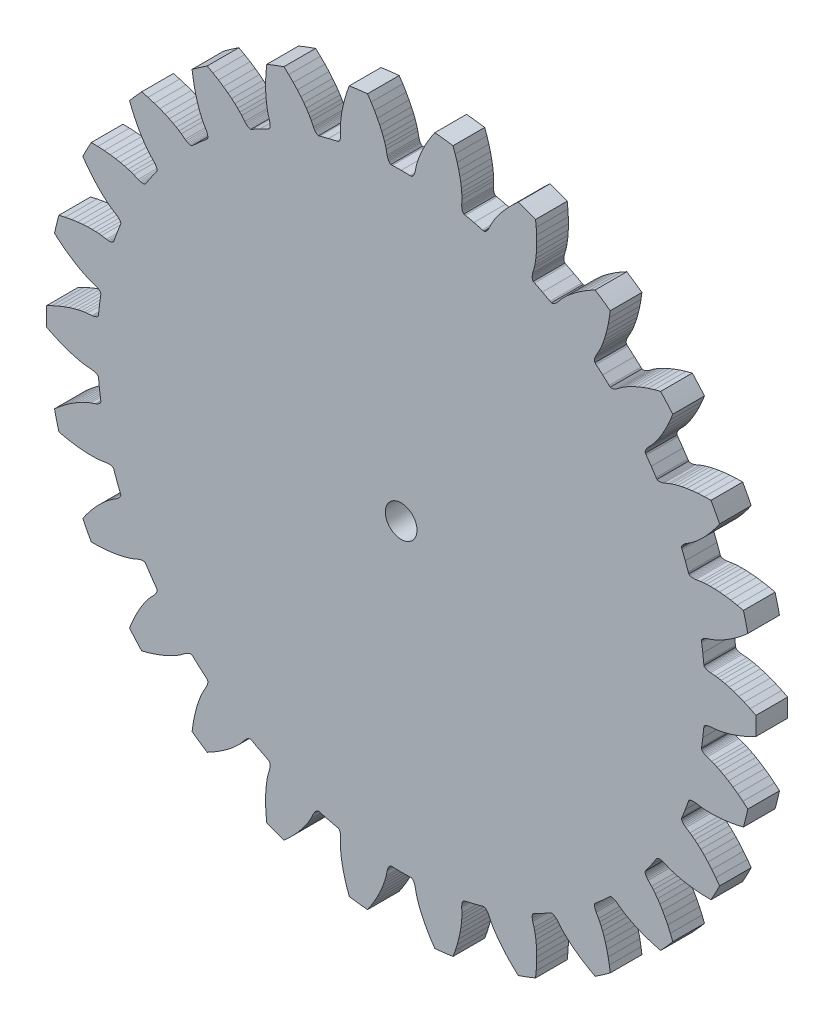
SolidWorks part; units mm, degrees
ref_plane "Front Plane" through (0, 0, 0) normal (0, 0, 1) x (1, 0, 0)
ref_plane "Top Plane" through (0, 0, 0) normal (0, 1, 0) x (1, 0, 0)
ref_plane "Right Plane" through (0, 0, 0) normal (1, 0, 0) x (0, 0, -1)
sketch "Model" plane through (0, 0, 0) normal (0, 0, 1) x (1, 0, 0)
  line L0 (53.9186, 11.3234) -> (53.1145, 10.6909)
  line L1 (53.1145, 10.6909) -> (52.3542, 10.1428)
  line L2 (52.3542, 10.1428) -> (51.6426, 9.6736)
  line L3 (51.6426, 9.6736) -> (50.9865, 9.2795)
  line L4 (50.9865, 9.2795) -> (50.3895, 8.954)
  line L5 (50.3895, 8.954) -> (49.8557, 8.6913)
  line L6 (49.8557, 8.6913) -> (49.3896, 8.4858)
  line L7 (49.3896, 8.4858) -> (48.9961, 8.3315)
  line L8 (48.9961, 8.3315) -> (48.275, 8.0914)
  line L9 (48.275, 8.0914) -> (48.0782, 8.0117)
  line L10 (48.0782, 8.0117) -> (47.9061, 7.9277)
  line L11 (47.9061, 7.9277) -> (47.7585, 7.8406)
  line L12 (47.7585, 7.8406) -> (47.6355, 7.7512)
  line L13 (47.6355, 7.7512) -> (47.5373, 7.6605)
  line L14 (47.5373, 7.6605) -> (47.4637, 7.5697)
  line L15 (47.4637, 7.5697) -> (47.4147, 7.4796)
  line L16 (47.4147, 7.4796) -> (47.3902, 7.3912)
  line L17 (47.3902, 7.3912) -> (47.3902, 7.3055)
  line L18 (47.3902, 7.3055) -> (47.4142, 7.1495)
  line L19 (47.4142, 7.1495) -> (47.6004, 5.7797)
  line L20 (47.6004, 5.7797) -> (47.7474, 4.4052)
  line L21 (47.7474, 4.4052) -> (47.7615, 4.248)
  line L22 (47.7615, 4.248) -> (47.782, 4.1648)
  line L23 (47.782, 4.1648) -> (47.8269, 4.0849)
  line L24 (47.8269, 4.0849) -> (47.896, 4.0091)
  line L25 (47.896, 4.0091) -> (47.9892, 3.9385)
  line L26 (47.9892, 3.9385) -> (48.1063, 3.874)
  line L27 (48.1063, 3.874) -> (48.2471, 3.8166)
  line L28 (48.2471, 3.8166) -> (48.4112, 3.7673)
  line L29 (48.4112, 3.7673) -> (48.5985, 3.727)
  line L30 (48.5985, 3.727) -> (48.8086, 3.6966)
  line L31 (48.8086, 3.6966) -> (49.5662, 3.6362)
  line L32 (49.5662, 3.6362) -> (49.9852, 3.5805)
  line L33 (49.9852, 3.5805) -> (50.4869, 3.4925)
  line L34 (50.4869, 3.4925) -> (51.0681, 3.3651)
  line L35 (51.0681, 3.3651) -> (51.7257, 3.192)
  line L36 (51.7257, 3.192) -> (52.457, 2.9663)
  line L37 (52.457, 2.9663) -> (53.2602, 2.6812)
  line L38 (53.2602, 2.6812) -> (54.1296, 2.3309)
  line L39 (54.1296, 2.3309) -> (55.0617, 1.9092)
  line L40 (55.0617, 1.9092) -> (55.9813, 1.447)
  line L41 (55.9813, -1.447) -> (55.0617, -1.9092)
  line L42 (55.0617, -1.9092) -> (54.1296, -2.3309)
  line L43 (54.1296, -2.3309) -> (53.2602, -2.6812)
  line L44 (53.2602, -2.6812) -> (52.457, -2.9663)
  line L45 (52.457, -2.9663) -> (51.7257, -3.192)
  line L46 (51.7257, -3.192) -> (51.0681, -3.3651)
  line L47 (51.0681, -3.3651) -> (50.4869, -3.4925)
  line L48 (50.4869, -3.4925) -> (49.9852, -3.5805)
  line L49 (49.9852, -3.5805) -> (49.5662, -3.6362)
  line L50 (49.5662, -3.6362) -> (48.8086, -3.6966)
  line L51 (48.8086, -3.6966) -> (48.5985, -3.727)
  line L52 (48.5985, -3.727) -> (48.4112, -3.7673)
  line L53 (48.4112, -3.7673) -> (48.2471, -3.8166)
  line L54 (48.2471, -3.8166) -> (48.1063, -3.874)
  line L55 (48.1063, -3.874) -> (47.9892, -3.9385)
  line L56 (47.9892, -3.9385) -> (47.896, -4.0091)
  line L57 (47.896, -4.0091) -> (47.8269, -4.0849)
  line L58 (47.8269, -4.0849) -> (47.782, -4.1648)
  line L59 (47.782, -4.1648) -> (47.7615, -4.248)
  line L60 (47.7615, -4.248) -> (47.7474, -4.4052)
  line L61 (47.7474, -4.4052) -> (47.6004, -5.7797)
  line L62 (47.6004, -5.7797) -> (47.4142, -7.1495)
  line L63 (47.4142, -7.1495) -> (47.3902, -7.3055)
  line L64 (47.3902, -7.3055) -> (47.3902, -7.3912)
  line L65 (47.3902, -7.3912) -> (47.4147, -7.4796)
  line L66 (47.4147, -7.4796) -> (47.4637, -7.5697)
  line L67 (47.4637, -7.5697) -> (47.5373, -7.6605)
  line L68 (47.5373, -7.6605) -> (47.6355, -7.7512)
  line L69 (47.6355, -7.7512) -> (47.7585, -7.8406)
  line L70 (47.7585, -7.8406) -> (47.9061, -7.9277)
  line L71 (47.9061, -7.9277) -> (48.0782, -8.0117)
  line L72 (48.0782, -8.0117) -> (48.275, -8.0914)
  line L73 (48.275, -8.0914) -> (48.9961, -8.3315)
  line L74 (48.9961, -8.3315) -> (49.3896, -8.4858)
  line L75 (49.3896, -8.4858) -> (49.8557, -8.6913)
  line L76 (49.8557, -8.6913) -> (50.3895, -8.954)
  line L77 (50.3895, -8.954) -> (50.9865, -9.2795)
  line L78 (50.9865, -9.2795) -> (51.6426, -9.6736)
  line L79 (51.6426, -9.6736) -> (52.3542, -10.1428)
  line L80 (52.3542, -10.1428) -> (53.1145, -10.6909)
  line L81 (53.1145, -10.6909) -> (53.9186, -11.3234)
  line L82 (53.9186, -11.3234) -> (54.7008, -11.9922)
  line L83 (54.0083, -14.8022) -> (53.0048, -15.0308)
  line L84 (53.0048, -15.0308) -> (51.9989, -15.2172)
  line L85 (51.9989, -15.2172) -> (51.0709, -15.3493)
  line L86 (51.0709, -15.3493) -> (50.2228, -15.4339)
  line L87 (50.2228, -15.4339) -> (49.4588, -15.478)
  line L88 (49.4588, -15.478) -> (48.7788, -15.4888)
  line L89 (48.7788, -15.4888) -> (48.1841, -15.4733)
  line L90 (48.1841, -15.4733) -> (47.6759, -15.4387)
  line L91 (47.6759, -15.4387) -> (47.2557, -15.3925)
  line L92 (47.2557, -15.3925) -> (46.5056, -15.2699)
  line L93 (46.5056, -15.2699) -> (46.2944, -15.2491)
  line L94 (46.2944, -15.2491) -> (46.1029, -15.2434)
  line L95 (46.1029, -15.2434) -> (45.9317, -15.252)
  line L96 (45.9317, -15.252) -> (45.7813, -15.274)
  line L97 (45.7813, -15.274) -> (45.6522, -15.3086)
  line L98 (45.6522, -15.3086) -> (45.5448, -15.3549)
  line L99 (45.5448, -15.3549) -> (45.4595, -15.4119)
  line L100 (45.4595, -15.4119) -> (45.3968, -15.4788)
  line L101 (45.3968, -15.4788) -> (45.357, -15.5546)
  line L102 (45.357, -15.5546) -> (45.3057, -15.7039)
  line L103 (45.3057, -15.7039) -> (44.834, -17.0033)
  line L104 (44.834, -17.0033) -> (44.3254, -18.2887)
  line L105 (44.3254, -18.2887) -> (44.2648, -18.4345)
  line L106 (44.2648, -18.4345) -> (44.2443, -18.5176)
  line L107 (44.2443, -18.5176) -> (44.2469, -18.6093)
  line L108 (44.2469, -18.6093) -> (44.2729, -18.7085)
  line L109 (44.2729, -18.7085) -> (44.3226, -18.8144)
  line L110 (44.3226, -18.8144) -> (44.3964, -18.9259)
  line L111 (44.3964, -18.9259) -> (44.4943, -19.0421)
  line L112 (44.4943, -19.0421) -> (44.6168, -19.162)
  line L113 (44.6168, -19.162) -> (44.7639, -19.2848)
  line L114 (44.7639, -19.2848) -> (44.9358, -19.4093)
  line L115 (44.9358, -19.4093) -> (45.5785, -19.8149)
  line L116 (45.5785, -19.8149) -> (45.9237, -20.0589)
  line L117 (45.9237, -20.0589) -> (46.327, -20.37)
  line L118 (46.327, -20.37) -> (46.7824, -20.7528)
  line L119 (46.7824, -20.7528) -> (47.2842, -21.2118)
  line L120 (47.2842, -21.2118) -> (47.8269, -21.7514)
  line L121 (47.8269, -21.7514) -> (48.4056, -22.3772)
  line L122 (48.4056, -22.3772) -> (49.0126, -23.0914)
  line L123 (49.0126, -23.0914) -> (49.6419, -23.8979)
  line L124 (49.6419, -23.8979) -> (50.2414, -24.7345)
  line L125 (48.8965, -27.2971) -> (47.8675, -27.2789)
  line L126 (47.8675, -27.2789) -> (46.8462, -27.2192)
  line L127 (46.8462, -27.2192) -> (45.9136, -27.1253)
  line L128 (45.9136, -27.1253) -> (45.0698, -27.0045)
  line L129 (45.0698, -27.0045) -> (44.3174, -26.8645)
  line L130 (44.3174, -26.8645) -> (43.6547, -26.7122)
  line L131 (43.6547, -26.7122) -> (43.0809, -26.5549)
  line L132 (43.0809, -26.5549) -> (42.5958, -26.3997)
  line L133 (42.5958, -26.3997) -> (42.1989, -26.2542)
  line L134 (42.1989, -26.2542) -> (41.4999, -25.9557)
  line L135 (41.4999, -25.9557) -> (41.2998, -25.8849)
  line L136 (41.2998, -25.8849) -> (41.1153, -25.8336)
  line L137 (41.1153, -25.8336) -> (40.947, -25.801)
  line L138 (40.947, -25.801) -> (40.7957, -25.7864)
  line L139 (40.7957, -25.7864) -> (40.662, -25.789)
  line L140 (40.662, -25.789) -> (40.5467, -25.8083)
  line L141 (40.5467, -25.8083) -> (40.4503, -25.8432)
  line L142 (40.4503, -25.8432) -> (40.3734, -25.8932)
  line L143 (40.3734, -25.8932) -> (40.3166, -25.9573)
  line L144 (40.3166, -25.9573) -> (40.231, -26.0899)
  line L145 (40.231, -26.0899) -> (39.4621, -27.2387)
  line L146 (39.4621, -27.2387) -> (38.6606, -28.3651)
  line L147 (38.6606, -28.3651) -> (38.5669, -28.4921)
  line L148 (38.5669, -28.4921) -> (38.5271, -28.5679)
  line L149 (38.5271, -28.5679) -> (38.5077, -28.6575)
  line L150 (38.5077, -28.6575) -> (38.5092, -28.7601)
  line L151 (38.5092, -28.7601) -> (38.5321, -28.8747)
  line L152 (38.5321, -28.8747) -> (38.577, -29.0007)
  line L153 (38.577, -29.0007) -> (38.6443, -29.1369)
  line L154 (38.6443, -29.1369) -> (38.7345, -29.2827)
  line L155 (38.7345, -29.2827) -> (38.848, -29.4371)
  line L156 (38.848, -29.4371) -> (38.9851, -29.5991)
  line L157 (38.9851, -29.5991) -> (39.5121, -30.1468)
  line L158 (39.5121, -30.1468) -> (39.7888, -30.4663)
  line L159 (39.7888, -30.4663) -> (40.1059, -30.8649)
  line L160 (40.1059, -30.8649) -> (40.4565, -31.3456)
  line L161 (40.4565, -31.3456) -> (40.8339, -31.9113)
  line L162 (40.8339, -31.9113) -> (41.2317, -32.5651)
  line L163 (41.2317, -32.5651) -> (41.6438, -33.3112)
  line L164 (41.6438, -33.3112) -> (42.0623, -34.1499)
  line L165 (42.0623, -34.1499) -> (42.4803, -35.0836)
  line L166 (42.4803, -35.0836) -> (42.8621, -36.0393)
  line L167 (40.943, -38.2055) -> (39.9482, -37.9417)
  line L168 (39.9482, -37.9417) -> (38.9709, -37.6393)
  line L169 (38.9709, -37.6393) -> (38.0879, -37.3249)
  line L170 (38.0879, -37.3249) -> (37.2976, -37.0058)
  line L171 (37.2976, -37.0058) -> (36.6006, -36.6897)
  line L172 (36.6006, -36.6897) -> (35.9935, -36.3833)
  line L173 (35.9935, -36.3833) -> (35.4741, -36.0932)
  line L174 (35.4741, -36.0932) -> (35.0402, -35.8264)
  line L175 (35.0402, -35.8264) -> (34.6896, -35.5902)
  line L176 (34.6896, -35.5902) -> (34.0824, -35.1331)
  line L177 (34.0824, -35.1331) -> (33.905, -35.0165)
  line L178 (33.905, -35.0165) -> (33.7381, -34.9224)
  line L179 (33.7381, -34.9224) -> (33.5826, -34.8505)
  line L180 (33.5826, -34.8505) -> (33.4392, -34.8001)
  line L181 (33.4392, -34.8001) -> (33.3087, -34.7707)
  line L182 (33.3087, -34.7707) -> (33.1922, -34.7618)
  line L183 (33.1922, -34.7618) -> (33.0902, -34.7727)
  line L184 (33.0902, -34.7727) -> (33.0035, -34.8027)
  line L185 (33.0035, -34.8027) -> (32.9331, -34.8514)
  line L186 (32.9331, -34.8514) -> (32.8183, -34.9597)
  line L187 (32.8183, -34.9597) -> (31.7967, -35.8911)
  line L188 (31.7967, -35.8911) -> (30.749, -36.7929)
  line L189 (30.749, -36.7929) -> (30.6276, -36.8938)
  line L190 (30.6276, -36.8938) -> (30.5708, -36.9579)
  line L191 (30.5708, -36.9579) -> (30.5305, -37.0403)
  line L192 (30.5305, -37.0403) -> (30.5074, -37.1402)
  line L193 (30.5074, -37.1402) -> (30.5023, -37.257)
  line L194 (30.5023, -37.257) -> (30.5157, -37.39)
  line L195 (30.5157, -37.39) -> (30.5485, -37.5385)
  line L196 (30.5485, -37.5385) -> (30.6011, -37.7016)
  line L197 (30.6011, -37.7016) -> (30.6744, -37.8786)
  line L198 (30.6744, -37.8786) -> (30.7687, -38.0687)
  line L199 (30.7687, -38.0687) -> (31.1493, -38.7266)
  line L200 (31.1493, -38.7266) -> (31.3416, -39.1031)
  line L201 (31.3416, -39.1031) -> (31.5541, -39.566)
  line L202 (31.5541, -39.566) -> (31.7795, -40.1166)
  line L203 (31.7795, -40.1166) -> (32.0105, -40.7562)
  line L204 (32.0105, -40.7562) -> (32.2402, -41.4862)
  line L205 (32.2402, -41.4862) -> (32.4618, -42.3092)
  line L206 (32.4618, -42.3092) -> (32.6674, -43.2237)
  line L207 (32.6674, -43.2237) -> (32.8498, -44.2303)
  line L208 (32.8498, -44.2303) -> (32.9918, -45.2497)
  line L209 (30.6101, -46.8937) -> (29.7074, -46.3994)
  line L210 (29.7074, -46.3994) -> (28.8309, -45.8719)
  line L211 (28.8309, -45.8719) -> (28.0487, -45.3554)
  line L212 (28.0487, -45.3554) -> (27.3577, -44.8563)
  line L213 (27.3577, -44.8563) -> (26.7566, -44.3827)
  line L214 (26.7566, -44.3827) -> (26.2405, -43.9399)
  line L215 (26.2405, -43.9399) -> (25.8056, -43.5339)
  line L216 (25.8056, -43.5339) -> (25.4481, -43.171)
  line L217 (25.4481, -43.171) -> (25.1643, -42.8578)
  line L218 (25.1643, -42.8578) -> (24.6842, -42.2686)
  line L219 (24.6842, -42.2686) -> (24.5398, -42.113)
  line L220 (24.5398, -42.113) -> (24.4003, -41.9817)
  line L221 (24.4003, -41.9817) -> (24.2664, -41.8746)
  line L222 (24.2664, -41.8746) -> (24.1393, -41.7914)
  line L223 (24.1393, -41.7914) -> (24.0197, -41.7317)
  line L224 (24.0197, -41.7317) -> (23.9086, -41.6951)
  line L225 (23.9086, -41.6951) -> (23.807, -41.6812)
  line L226 (23.807, -41.6812) -> (23.7157, -41.6897)
  line L227 (23.7157, -41.6897) -> (23.6356, -41.72)
  line L228 (23.6356, -41.72) -> (23.4982, -41.7978)
  line L229 (23.4982, -41.7978) -> (22.2835, -42.4576)
  line L230 (22.2835, -42.4576) -> (21.0504, -43.0825)
  line L231 (21.0504, -43.0825) -> (20.9084, -43.1514)
  line L232 (20.9084, -43.1514) -> (20.8379, -43.2001)
  line L233 (20.8379, -43.2001) -> (20.7791, -43.2704)
  line L234 (20.7791, -43.2704) -> (20.7327, -43.3619)
  line L235 (20.7327, -43.3619) -> (20.6997, -43.4741)
  line L236 (20.6997, -43.4741) -> (20.681, -43.6064)
  line L237 (20.681, -43.6064) -> (20.6772, -43.7584)
  line L238 (20.6772, -43.7584) -> (20.6893, -43.9294)
  line L239 (20.6893, -43.9294) -> (20.7181, -44.1188)
  line L240 (20.7181, -44.1188) -> (20.7642, -44.326)
  line L241 (20.7642, -44.326) -> (20.9763, -45.0558)
  line L242 (20.9763, -45.0558) -> (21.0729, -45.4673)
  line L243 (21.0729, -45.4673) -> (21.1684, -45.9677)
  line L244 (21.1684, -45.9677) -> (21.2555, -46.5562)
  line L245 (21.2555, -46.5562) -> (21.3267, -47.2325)
  line L246 (21.3267, -47.2325) -> (21.3751, -47.9962)
  line L247 (21.3751, -47.9962) -> (21.3933, -48.8484)
  line L248 (21.3933, -48.8484) -> (21.374, -49.7855)
  line L249 (21.374, -49.7855) -> (21.3103, -50.8066)
  line L250 (21.3103, -50.8066) -> (21.2042, -51.8303)
  line L251 (18.4982, -52.8565) -> (17.74, -52.1606)
  line L252 (17.74, -52.1606) -> (17.0152, -51.4386)
  line L253 (17.0152, -51.4386) -> (16.3794, -50.7499)
  line L254 (16.3794, -50.7499) -> (15.8279, -50.1)
  line L255 (15.8279, -50.1) -> (15.3576, -49.4963)
  line L256 (15.3576, -49.4963) -> (14.9625, -48.9428)
  line L257 (14.9625, -48.9428) -> (14.6374, -48.4445)
  line L258 (14.6374, -48.4445) -> (14.3772, -48.0067)
  line L259 (14.3772, -48.0067) -> (14.1765, -47.6346)
  line L260 (14.1765, -47.6346) -> (13.8513, -46.9477)
  line L261 (13.8513, -46.9477) -> (13.7485, -46.762)
  line L262 (13.7485, -46.762) -> (13.6444, -46.6012)
  line L263 (13.6444, -46.6012) -> (13.54, -46.4652)
  line L264 (13.54, -46.4652) -> (13.4365, -46.3539)
  line L265 (13.4365, -46.3539) -> (13.3347, -46.2673)
  line L266 (13.3347, -46.2673) -> (13.2356, -46.2052)
  line L267 (13.2356, -46.2052) -> (13.1402, -46.1674)
  line L268 (13.1402, -46.1674) -> (13.0496, -46.1538)
  line L269 (13.0496, -46.1538) -> (12.9645, -46.1641)
  line L270 (12.9645, -46.1641) -> (12.8126, -46.2067)
  line L271 (12.8126, -46.2067) -> (11.4752, -46.5567)
  line L272 (11.4752, -46.5567) -> (10.1284, -46.8683)
  line L273 (10.1284, -46.8683) -> (9.974, -46.9012)
  line L274 (9.974, -46.9012) -> (9.8939, -46.9316)
  line L275 (9.8939, -46.9316) -> (9.82, -46.9858)
  line L276 (9.82, -46.9858) -> (9.7531, -47.0635)
  line L277 (9.7531, -47.0635) -> (9.6942, -47.1646)
  line L278 (9.6942, -47.1646) -> (9.6443, -47.2886)
  line L279 (9.6443, -47.2886) -> (9.6043, -47.4353)
  line L280 (9.6043, -47.4353) -> (9.5752, -47.6042)
  line L281 (9.5752, -47.6042) -> (9.5577, -47.7949)
  line L282 (9.5577, -47.7949) -> (9.5529, -48.0071)
  line L283 (9.5529, -48.0071) -> (9.5842, -48.7665)
  line L284 (9.5842, -48.7665) -> (9.5795, -49.1892)
  line L285 (9.5795, -49.1892) -> (9.5525, -49.6979)
  line L286 (9.5525, -49.6979) -> (9.4962, -50.2901)
  line L287 (9.4962, -50.2901) -> (9.4036, -50.9638)
  line L288 (9.4036, -50.9638) -> (9.2677, -51.717)
  line L289 (9.2677, -51.717) -> (9.0814, -52.5487)
  line L290 (9.0814, -52.5487) -> (8.8385, -53.454)
  line L291 (8.8385, -53.454) -> (8.5322, -54.4301)
  line L292 (8.5322, -54.4301) -> (8.1843, -55.3987)
  line L293 (5.3113, -55.7475) -> (4.7417, -54.8903)
  line L294 (4.7417, -54.8903) -> (4.2107, -54.0159)
  line L295 (4.2107, -54.0159) -> (3.7582, -53.1951)
  line L296 (3.7582, -53.1951) -> (3.3783, -52.4321)
  line L297 (3.3783, -52.4321) -> (3.0661, -51.7333)
  line L298 (3.0661, -51.7333) -> (2.815, -51.1014)
  line L299 (2.815, -51.1014) -> (2.6185, -50.5398)
  line L300 (2.6185, -50.5398) -> (2.4706, -50.0524)
  line L301 (2.4706, -50.0524) -> (2.3649, -49.6431)
  line L302 (2.3649, -49.6431) -> (2.2135, -48.8983)
  line L303 (2.2135, -48.8983) -> (2.1581, -48.6934)
  line L304 (2.1581, -48.6934) -> (2.0955, -48.5123)
  line L305 (2.0955, -48.5123) -> (2.0267, -48.3553)
  line L306 (2.0267, -48.3553) -> (1.9528, -48.2225)
  line L307 (1.9528, -48.2225) -> (1.8747, -48.114)
  line L308 (1.8747, -48.114) -> (1.7934, -48.03)
  line L309 (1.7934, -48.03) -> (1.7098, -47.9705)
  line L310 (1.7098, -47.9705) -> (1.625, -47.9356)
  line L311 (1.625, -47.9356) -> (1.54, -47.9253)
  line L312 (1.54, -47.9253) -> (1.3823, -47.9302)
  line L313 (1.3823, -47.9302) -> (0, -47.95)
  line L314 (0, -47.95) -> (-1.3823, -47.9302)
  line L315 (-1.3823, -47.9302) -> (-1.54, -47.9253)
  line L316 (-1.54, -47.9253) -> (-1.625, -47.9356)
  line L317 (-1.625, -47.9356) -> (-1.7098, -47.9705)
  line L318 (-1.7098, -47.9705) -> (-1.7934, -48.03)
  line L319 (-1.7934, -48.03) -> (-1.8747, -48.114)
  line L320 (-1.8747, -48.114) -> (-1.9528, -48.2225)
  line L321 (-1.9528, -48.2225) -> (-2.0267, -48.3553)
  line L322 (-2.0267, -48.3553) -> (-2.0955, -48.5123)
  line L323 (-2.0955, -48.5123) -> (-2.1581, -48.6934)
  line L324 (-2.1581, -48.6934) -> (-2.2135, -48.8983)
  line L325 (-2.2135, -48.8983) -> (-2.3649, -49.6431)
  line L326 (-2.3649, -49.6431) -> (-2.4706, -50.0524)
  line L327 (-2.4706, -50.0524) -> (-2.6185, -50.5398)
  line L328 (-2.6185, -50.5398) -> (-2.815, -51.1014)
  line L329 (-2.815, -51.1014) -> (-3.0661, -51.7333)
  line L330 (-3.0661, -51.7333) -> (-3.3783, -52.4321)
  line L331 (-3.3783, -52.4321) -> (-3.7582, -53.1951)
  line L332 (-3.7582, -53.1951) -> (-4.2107, -54.0159)
  line L333 (-4.2107, -54.0159) -> (-4.7417, -54.8903)
  line L334 (-4.7417, -54.8903) -> (-5.3113, -55.7475)
  line L335 (-8.1843, -55.3987) -> (-8.5322, -54.4301)
  line L336 (-8.5322, -54.4301) -> (-8.8385, -53.454)
  line L337 (-8.8385, -53.454) -> (-9.0814, -52.5487)
  line L338 (-9.0814, -52.5487) -> (-9.2677, -51.717)
  line L339 (-9.2677, -51.717) -> (-9.4036, -50.9638)
  line L340 (-9.4036, -50.9638) -> (-9.4962, -50.2901)
  line L341 (-9.4962, -50.2901) -> (-9.5525, -49.6979)
  line L342 (-9.5525, -49.6979) -> (-9.5795, -49.1892)
  line L343 (-9.5795, -49.1892) -> (-9.5842, -48.7665)
  line L344 (-9.5842, -48.7665) -> (-9.5529, -48.0071)
  line L345 (-9.5529, -48.0071) -> (-9.5577, -47.7949)
  line L346 (-9.5577, -47.7949) -> (-9.5752, -47.6042)
  line L347 (-9.5752, -47.6042) -> (-9.6043, -47.4353)
  line L348 (-9.6043, -47.4353) -> (-9.6443, -47.2886)
  line L349 (-9.6443, -47.2886) -> (-9.6942, -47.1646)
  line L350 (-9.6942, -47.1646) -> (-9.7531, -47.0635)
  line L351 (-9.7531, -47.0635) -> (-9.82, -46.9858)
  line L352 (-9.82, -46.9858) -> (-9.8939, -46.9316)
  line L353 (-9.8939, -46.9316) -> (-9.974, -46.9012)
  line L354 (-9.974, -46.9012) -> (-10.1284, -46.8683)
  line L355 (-10.1284, -46.8683) -> (-11.4752, -46.5567)
  line L356 (-11.4752, -46.5567) -> (-12.8126, -46.2067)
  line L357 (-12.8126, -46.2067) -> (-12.9645, -46.1641)
  line L358 (-12.9645, -46.1641) -> (-13.0496, -46.1538)
  line L359 (-13.0496, -46.1538) -> (-13.1402, -46.1674)
  line L360 (-13.1402, -46.1674) -> (-13.2356, -46.2052)
  line L361 (-13.2356, -46.2052) -> (-13.3347, -46.2673)
  line L362 (-13.3347, -46.2673) -> (-13.4365, -46.3539)
  line L363 (-13.4365, -46.3539) -> (-13.54, -46.4652)
  line L364 (-13.54, -46.4652) -> (-13.6444, -46.6012)
  line L365 (-13.6444, -46.6012) -> (-13.7485, -46.762)
  line L366 (-13.7485, -46.762) -> (-13.8513, -46.9477)
  line L367 (-13.8513, -46.9477) -> (-14.1765, -47.6346)
  line L368 (-14.1765, -47.6346) -> (-14.3772, -48.0067)
  line L369 (-14.3772, -48.0067) -> (-14.6374, -48.4445)
  line L370 (-14.6374, -48.4445) -> (-14.9625, -48.9428)
  line L371 (-14.9625, -48.9428) -> (-15.3576, -49.4963)
  line L372 (-15.3576, -49.4963) -> (-15.8279, -50.1)
  line L373 (-15.8279, -50.1) -> (-16.3794, -50.7499)
  line L374 (-16.3794, -50.7499) -> (-17.0152, -51.4386)
  line L375 (-17.0152, -51.4386) -> (-17.74, -52.1606)
  line L376 (-17.74, -52.1606) -> (-18.4982, -52.8565)
  line L377 (-21.2042, -51.8303) -> (-21.3103, -50.8066)
  line L378 (-21.3103, -50.8066) -> (-21.374, -49.7855)
  line L379 (-21.374, -49.7855) -> (-21.3933, -48.8484)
  line L380 (-21.3933, -48.8484) -> (-21.3751, -47.9962)
  line L381 (-21.3751, -47.9962) -> (-21.3267, -47.2325)
  line L382 (-21.3267, -47.2325) -> (-21.2555, -46.5562)
  line L383 (-21.2555, -46.5562) -> (-21.1684, -45.9677)
  line L384 (-21.1684, -45.9677) -> (-21.0729, -45.4673)
  line L385 (-21.0729, -45.4673) -> (-20.9763, -45.0558)
  line L386 (-20.9763, -45.0558) -> (-20.7642, -44.326)
  line L387 (-20.7642, -44.326) -> (-20.7181, -44.1188)
  line L388 (-20.7181, -44.1188) -> (-20.6893, -43.9294)
  line L389 (-20.6893, -43.9294) -> (-20.6772, -43.7584)
  line L390 (-20.6772, -43.7584) -> (-20.681, -43.6064)
  line L391 (-20.681, -43.6064) -> (-20.6997, -43.4741)
  line L392 (-20.6997, -43.4741) -> (-20.7327, -43.3619)
  line L393 (-20.7327, -43.3619) -> (-20.7791, -43.2704)
  line L394 (-20.7791, -43.2704) -> (-20.8379, -43.2001)
  line L395 (-20.8379, -43.2001) -> (-20.9084, -43.1514)
  line L396 (-20.9084, -43.1514) -> (-21.0504, -43.0825)
  line L397 (-21.0504, -43.0825) -> (-22.2835, -42.4576)
  line L398 (-22.2835, -42.4576) -> (-23.4982, -41.7978)
  line L399 (-23.4982, -41.7978) -> (-23.6356, -41.72)
  line L400 (-23.6356, -41.72) -> (-23.7157, -41.6897)
  line L401 (-23.7157, -41.6897) -> (-23.807, -41.6812)
  line L402 (-23.807, -41.6812) -> (-23.9086, -41.6951)
  line L403 (-23.9086, -41.6951) -> (-24.0197, -41.7317)
  line L404 (-24.0197, -41.7317) -> (-24.1393, -41.7914)
  line L405 (-24.1393, -41.7914) -> (-24.2664, -41.8746)
  line L406 (-24.2664, -41.8746) -> (-24.4003, -41.9817)
  line L407 (-24.4003, -41.9817) -> (-24.5398, -42.113)
  line L408 (-24.5398, -42.113) -> (-24.6842, -42.2686)
  line L409 (-24.6842, -42.2686) -> (-25.1643, -42.8578)
  line L410 (-25.1643, -42.8578) -> (-25.4481, -43.171)
  line L411 (-25.4481, -43.171) -> (-25.8056, -43.5339)
  line L412 (-25.8056, -43.5339) -> (-26.2405, -43.9399)
  line L413 (-26.2405, -43.9399) -> (-26.7566, -44.3827)
  line L414 (-26.7566, -44.3827) -> (-27.3577, -44.8563)
  line L415 (-27.3577, -44.8563) -> (-28.0487, -45.3554)
  line L416 (-28.0487, -45.3554) -> (-28.8309, -45.8719)
  line L417 (-28.8309, -45.8719) -> (-29.7074, -46.3994)
  line L418 (-29.7074, -46.3994) -> (-30.6101, -46.8937)
  line L419 (-32.9918, -45.2497) -> (-32.8498, -44.2303)
  line L420 (-32.8498, -44.2303) -> (-32.6674, -43.2237)
  line L421 (-32.6674, -43.2237) -> (-32.4618, -42.3092)
  line L422 (-32.4618, -42.3092) -> (-32.2402, -41.4862)
  line L423 (-32.2402, -41.4862) -> (-32.0105, -40.7562)
  line L424 (-32.0105, -40.7562) -> (-31.7795, -40.1166)
  line L425 (-31.7795, -40.1166) -> (-31.5541, -39.566)
  line L426 (-31.5541, -39.566) -> (-31.3416, -39.1031)
  line L427 (-31.3416, -39.1031) -> (-31.1493, -38.7266)
  line L428 (-31.1493, -38.7266) -> (-30.7687, -38.0687)
  line L429 (-30.7687, -38.0687) -> (-30.6744, -37.8786)
  line L430 (-30.6744, -37.8786) -> (-30.6011, -37.7016)
  line L431 (-30.6011, -37.7016) -> (-30.5485, -37.5385)
  line L432 (-30.5485, -37.5385) -> (-30.5157, -37.39)
  line L433 (-30.5157, -37.39) -> (-30.5023, -37.257)
  line L434 (-30.5023, -37.257) -> (-30.5074, -37.1402)
  line L435 (-30.5074, -37.1402) -> (-30.5305, -37.0403)
  line L436 (-30.5305, -37.0403) -> (-30.5708, -36.9579)
  line L437 (-30.5708, -36.9579) -> (-30.6276, -36.8938)
  line L438 (-30.6276, -36.8938) -> (-30.749, -36.7929)
  line L439 (-30.749, -36.7929) -> (-31.7967, -35.8911)
  line L440 (-31.7967, -35.8911) -> (-32.8183, -34.9597)
  line L441 (-32.8183, -34.9597) -> (-32.9331, -34.8514)
  line L442 (-32.9331, -34.8514) -> (-33.0035, -34.8027)
  line L443 (-33.0035, -34.8027) -> (-33.0902, -34.7727)
  line L444 (-33.0902, -34.7727) -> (-33.1922, -34.7618)
  line L445 (-33.1922, -34.7618) -> (-33.3087, -34.7707)
  line L446 (-33.3087, -34.7707) -> (-33.4392, -34.8001)
  line L447 (-33.4392, -34.8001) -> (-33.5826, -34.8505)
  line L448 (-33.5826, -34.8505) -> (-33.7381, -34.9224)
  line L449 (-33.7381, -34.9224) -> (-33.905, -35.0165)
  line L450 (-33.905, -35.0165) -> (-34.0824, -35.1331)
  line L451 (-34.0824, -35.1331) -> (-34.6896, -35.5902)
  line L452 (-34.6896, -35.5902) -> (-35.0402, -35.8264)
  line L453 (-35.0402, -35.8264) -> (-35.4741, -36.0932)
  line L454 (-35.4741, -36.0932) -> (-35.9935, -36.3833)
  line L455 (-35.9935, -36.3833) -> (-36.6006, -36.6897)
  line L456 (-36.6006, -36.6897) -> (-37.2976, -37.0058)
  line L457 (-37.2976, -37.0058) -> (-38.0879, -37.3249)
  line L458 (-38.0879, -37.3249) -> (-38.9709, -37.6393)
  line L459 (-38.9709, -37.6393) -> (-39.9482, -37.9417)
  line L460 (-39.9482, -37.9417) -> (-40.943, -38.2055)
  line L461 (-42.8621, -36.0393) -> (-42.4803, -35.0836)
  line L462 (-42.4803, -35.0836) -> (-42.0623, -34.1499)
  line L463 (-42.0623, -34.1499) -> (-41.6438, -33.3112)
  line L464 (-41.6438, -33.3112) -> (-41.2317, -32.5651)
  line L465 (-41.2317, -32.5651) -> (-40.8339, -31.9113)
  line L466 (-40.8339, -31.9113) -> (-40.4565, -31.3456)
  line L467 (-40.4565, -31.3456) -> (-40.1059, -30.8649)
  line L468 (-40.1059, -30.8649) -> (-39.7888, -30.4663)
  line L469 (-39.7888, -30.4663) -> (-39.5121, -30.1468)
  line L470 (-39.5121, -30.1468) -> (-38.9851, -29.5991)
  line L471 (-38.9851, -29.5991) -> (-38.848, -29.4371)
  line L472 (-38.848, -29.4371) -> (-38.7345, -29.2827)
  line L473 (-38.7345, -29.2827) -> (-38.6443, -29.1369)
  line L474 (-38.6443, -29.1369) -> (-38.577, -29.0007)
  line L475 (-38.577, -29.0007) -> (-38.5321, -28.8747)
  line L476 (-38.5321, -28.8747) -> (-38.5092, -28.7601)
  line L477 (-38.5092, -28.7601) -> (-38.5077, -28.6575)
  line L478 (-38.5077, -28.6575) -> (-38.5271, -28.5679)
  line L479 (-38.5271, -28.5679) -> (-38.5669, -28.4921)
  line L480 (-38.5669, -28.4921) -> (-38.6606, -28.3651)
  line L481 (-38.6606, -28.3651) -> (-39.4621, -27.2387)
  line L482 (-39.4621, -27.2387) -> (-40.231, -26.0899)
  line L483 (-40.231, -26.0899) -> (-40.3166, -25.9573)
  line L484 (-40.3166, -25.9573) -> (-40.3734, -25.8932)
  line L485 (-40.3734, -25.8932) -> (-40.4503, -25.8432)
  line L486 (-40.4503, -25.8432) -> (-40.5467, -25.8083)
  line L487 (-40.5467, -25.8083) -> (-40.662, -25.789)
  line L488 (-40.662, -25.789) -> (-40.7957, -25.7864)
  line L489 (-40.7957, -25.7864) -> (-40.947, -25.801)
  line L490 (-40.947, -25.801) -> (-41.1153, -25.8336)
  line L491 (-41.1153, -25.8336) -> (-41.2998, -25.8849)
  line L492 (-41.2998, -25.8849) -> (-41.4999, -25.9557)
  line L493 (-41.4999, -25.9557) -> (-42.1989, -26.2542)
  line L494 (-42.1989, -26.2542) -> (-42.5958, -26.3997)
  line L495 (-42.5958, -26.3997) -> (-43.0809, -26.5549)
  line L496 (-43.0809, -26.5549) -> (-43.6547, -26.7122)
  line L497 (-43.6547, -26.7122) -> (-44.3174, -26.8645)
  line L498 (-44.3174, -26.8645) -> (-45.0698, -27.0045)
  line L499 (-45.0698, -27.0045) -> (-45.9136, -27.1253)
  line L500 (-45.9136, -27.1253) -> (-46.8462, -27.2192)
  line L501 (-46.8462, -27.2192) -> (-47.8675, -27.2789)
  line L502 (-47.8675, -27.2789) -> (-48.8965, -27.2971)
  line L503 (-50.2414, -24.7345) -> (-49.6419, -23.8979)
  line L504 (-49.6419, -23.8979) -> (-49.0126, -23.0914)
  line L505 (-49.0126, -23.0914) -> (-48.4056, -22.3772)
  line L506 (-48.4056, -22.3772) -> (-47.8269, -21.7514)
  line L507 (-47.8269, -21.7514) -> (-47.2842, -21.2118)
  line L508 (-47.2842, -21.2118) -> (-46.7824, -20.7528)
  line L509 (-46.7824, -20.7528) -> (-46.327, -20.37)
  line L510 (-46.327, -20.37) -> (-45.9237, -20.0589)
  line L511 (-45.9237, -20.0589) -> (-45.5785, -19.8149)
  line L512 (-45.5785, -19.8149) -> (-44.9358, -19.4093)
  line L513 (-44.9358, -19.4093) -> (-44.7639, -19.2848)
  line L514 (-44.7639, -19.2848) -> (-44.6168, -19.162)
  line L515 (-44.6168, -19.162) -> (-44.4943, -19.0421)
  line L516 (-44.4943, -19.0421) -> (-44.3964, -18.9259)
  line L517 (-44.3964, -18.9259) -> (-44.3226, -18.8144)
  line L518 (-44.3226, -18.8144) -> (-44.2729, -18.7085)
  line L519 (-44.2729, -18.7085) -> (-44.2469, -18.6093)
  line L520 (-44.2469, -18.6093) -> (-44.2443, -18.5176)
  line L521 (-44.2443, -18.5176) -> (-44.2648, -18.4345)
  line L522 (-44.2648, -18.4345) -> (-44.3254, -18.2887)
  line L523 (-44.3254, -18.2887) -> (-44.834, -17.0033)
  line L524 (-44.834, -17.0033) -> (-45.3057, -15.7039)
  line L525 (-45.3057, -15.7039) -> (-45.357, -15.5546)
  line L526 (-45.357, -15.5546) -> (-45.3968, -15.4788)
  line L527 (-45.3968, -15.4788) -> (-45.4595, -15.4119)
  line L528 (-45.4595, -15.4119) -> (-45.5448, -15.3549)
  line L529 (-45.5448, -15.3549) -> (-45.6522, -15.3086)
  line L530 (-45.6522, -15.3086) -> (-45.7813, -15.274)
  line L531 (-45.7813, -15.274) -> (-45.9317, -15.252)
  line L532 (-45.9317, -15.252) -> (-46.1029, -15.2434)
  line L533 (-46.1029, -15.2434) -> (-46.2944, -15.2491)
  line L534 (-46.2944, -15.2491) -> (-46.5056, -15.2699)
  line L535 (-46.5056, -15.2699) -> (-47.2557, -15.3925)
  line L536 (-47.2557, -15.3925) -> (-47.6759, -15.4387)
  line L537 (-47.6759, -15.4387) -> (-48.1841, -15.4733)
  line L538 (-48.1841, -15.4733) -> (-48.7788, -15.4888)
  line L539 (-48.7788, -15.4888) -> (-49.4588, -15.478)
  line L540 (-49.4588, -15.478) -> (-50.2228, -15.4339)
  line L541 (-50.2228, -15.4339) -> (-51.0709, -15.3493)
  line L542 (-51.0709, -15.3493) -> (-51.9989, -15.2172)
  line L543 (-51.9989, -15.2172) -> (-53.0048, -15.0308)
  line L544 (-53.0048, -15.0308) -> (-54.0083, -14.8022)
  line L545 (-54.7008, -11.9922) -> (-53.9186, -11.3234)
  line L546 (-53.9186, -11.3234) -> (-53.1145, -10.6909)
  line L547 (-53.1145, -10.6909) -> (-52.3542, -10.1428)
  line L548 (-52.3542, -10.1428) -> (-51.6426, -9.6736)
  line L549 (-51.6426, -9.6736) -> (-50.9865, -9.2795)
  line L550 (-50.9865, -9.2795) -> (-50.3895, -8.954)
  line L551 (-50.3895, -8.954) -> (-49.8557, -8.6913)
  line L552 (-49.8557, -8.6913) -> (-49.3896, -8.4858)
  line L553 (-49.3896, -8.4858) -> (-48.9961, -8.3315)
  line L554 (-48.9961, -8.3315) -> (-48.275, -8.0914)
  line L555 (-48.275, -8.0914) -> (-48.0782, -8.0117)
  line L556 (-48.0782, -8.0117) -> (-47.9061, -7.9277)
  line L557 (-47.9061, -7.9277) -> (-47.7585, -7.8406)
  line L558 (-47.7585, -7.8406) -> (-47.6355, -7.7512)
  line L559 (-47.6355, -7.7512) -> (-47.5373, -7.6605)
  line L560 (-47.5373, -7.6605) -> (-47.4637, -7.5697)
  line L561 (-47.4637, -7.5697) -> (-47.4147, -7.4796)
  line L562 (-47.4147, -7.4796) -> (-47.3902, -7.3912)
  line L563 (-47.3902, -7.3912) -> (-47.3902, -7.3055)
  line L564 (-47.3902, -7.3055) -> (-47.4142, -7.1495)
  line L565 (-47.4142, -7.1495) -> (-47.6004, -5.7797)
  line L566 (-47.6004, -5.7797) -> (-47.7474, -4.4052)
  line L567 (-47.7474, -4.4052) -> (-47.7615, -4.248)
  line L568 (-47.7615, -4.248) -> (-47.782, -4.1648)
  line L569 (-47.782, -4.1648) -> (-47.8269, -4.0849)
  line L570 (-47.8269, -4.0849) -> (-47.896, -4.0091)
  line L571 (-47.896, -4.0091) -> (-47.9892, -3.9385)
  line L572 (-47.9892, -3.9385) -> (-48.1063, -3.874)
  line L573 (-48.1063, -3.874) -> (-48.2471, -3.8166)
  line L574 (-48.2471, -3.8166) -> (-48.4112, -3.7673)
  line L575 (-48.4112, -3.7673) -> (-48.5985, -3.727)
  line L576 (-48.5985, -3.727) -> (-48.8086, -3.6966)
  line L577 (-48.8086, -3.6966) -> (-49.5662, -3.6362)
  line L578 (-49.5662, -3.6362) -> (-49.9852, -3.5805)
  line L579 (-49.9852, -3.5805) -> (-50.4869, -3.4925)
  line L580 (-50.4869, -3.4925) -> (-51.0681, -3.3651)
  line L581 (-51.0681, -3.3651) -> (-51.7257, -3.192)
  line L582 (-51.7257, -3.192) -> (-52.457, -2.9663)
  line L583 (-52.457, -2.9663) -> (-53.2602, -2.6812)
  line L584 (-53.2602, -2.6812) -> (-54.1296, -2.3309)
  line L585 (-54.1296, -2.3309) -> (-55.0617, -1.9092)
  line L586 (-55.0617, -1.9092) -> (-55.9813, -1.447)
  line L587 (-55.9813, 1.447) -> (-55.0617, 1.9092)
  line L588 (-55.0617, 1.9092) -> (-54.1296, 2.3309)
  line L589 (-54.1296, 2.3309) -> (-53.2602, 2.6812)
  line L590 (-53.2602, 2.6812) -> (-52.457, 2.9663)
  line L591 (-52.457, 2.9663) -> (-51.7257, 3.192)
  line L592 (-51.7257, 3.192) -> (-51.0681, 3.3651)
  line L593 (-51.0681, 3.3651) -> (-50.4869, 3.4925)
  line L594 (-50.4869, 3.4925) -> (-49.9852, 3.5805)
  line L595 (-49.9852, 3.5805) -> (-49.5662, 3.6362)
  line L596 (-49.5662, 3.6362) -> (-48.8086, 3.6966)
  line L597 (-48.8086, 3.6966) -> (-48.5985, 3.727)
  line L598 (-48.5985, 3.727) -> (-48.4112, 3.7673)
  line L599 (-48.4112, 3.7673) -> (-48.2471, 3.8166)
  line L600 (-48.2471, 3.8166) -> (-48.1063, 3.874)
  line L601 (-48.1063, 3.874) -> (-47.9892, 3.9385)
  line L602 (-47.9892, 3.9385) -> (-47.896, 4.0091)
  line L603 (-47.896, 4.0091) -> (-47.8269, 4.0849)
  line L604 (-47.8269, 4.0849) -> (-47.782, 4.1648)
  line L605 (-47.782, 4.1648) -> (-47.7615, 4.248)
  line L606 (-47.7615, 4.248) -> (-47.7474, 4.4052)
  line L607 (-47.7474, 4.4052) -> (-47.6004, 5.7797)
  line L608 (-47.6004, 5.7797) -> (-47.4142, 7.1495)
  line L609 (-47.4142, 7.1495) -> (-47.3902, 7.3055)
  line L610 (-47.3902, 7.3055) -> (-47.3902, 7.3912)
  line L611 (-47.3902, 7.3912) -> (-47.4147, 7.4796)
  line L612 (-47.4147, 7.4796) -> (-47.4637, 7.5697)
  line L613 (-47.4637, 7.5697) -> (-47.5373, 7.6605)
  line L614 (-47.5373, 7.6605) -> (-47.6355, 7.7512)
  line L615 (-47.6355, 7.7512) -> (-47.7585, 7.8406)
  line L616 (-47.7585, 7.8406) -> (-47.9061, 7.9277)
  line L617 (-47.9061, 7.9277) -> (-48.0782, 8.0117)
  line L618 (-48.0782, 8.0117) -> (-48.275, 8.0914)
  line L619 (-48.275, 8.0914) -> (-48.9961, 8.3315)
  line L620 (-48.9961, 8.3315) -> (-49.3896, 8.4858)
  line L621 (-49.3896, 8.4858) -> (-49.8557, 8.6913)
  line L622 (-49.8557, 8.6913) -> (-50.3895, 8.954)
  line L623 (-50.3895, 8.954) -> (-50.9865, 9.2795)
  line L624 (-50.9865, 9.2795) -> (-51.6426, 9.6736)
  line L625 (-51.6426, 9.6736) -> (-52.3542, 10.1428)
  line L626 (-52.3542, 10.1428) -> (-53.1145, 10.6909)
  line L627 (-53.1145, 10.6909) -> (-53.9186, 11.3234)
  line L628 (-53.9186, 11.3234) -> (-54.7008, 11.9922)
  line L629 (-54.0083, 14.8022) -> (-53.0048, 15.0308)
  line L630 (-53.0048, 15.0308) -> (-51.9989, 15.2172)
  line L631 (-51.9989, 15.2172) -> (-51.0709, 15.3493)
  line L632 (-51.0709, 15.3493) -> (-50.2228, 15.4339)
  line L633 (-50.2228, 15.4339) -> (-49.4588, 15.478)
  line L634 (-49.4588, 15.478) -> (-48.7788, 15.4888)
  line L635 (-48.7788, 15.4888) -> (-48.1841, 15.4733)
  line L636 (-48.1841, 15.4733) -> (-47.6759, 15.4387)
  line L637 (-47.6759, 15.4387) -> (-47.2557, 15.3925)
  line L638 (-47.2557, 15.3925) -> (-46.5056, 15.2699)
  line L639 (-46.5056, 15.2699) -> (-46.2944, 15.2491)
  line L640 (-46.2944, 15.2491) -> (-46.1029, 15.2434)
  line L641 (-46.1029, 15.2434) -> (-45.9317, 15.252)
  line L642 (-45.9317, 15.252) -> (-45.7813, 15.274)
  line L643 (-45.7813, 15.274) -> (-45.6522, 15.3086)
  line L644 (-45.6522, 15.3086) -> (-45.5448, 15.3549)
  line L645 (-45.5448, 15.3549) -> (-45.4595, 15.4119)
  line L646 (-45.4595, 15.4119) -> (-45.3968, 15.4788)
  line L647 (-45.3968, 15.4788) -> (-45.357, 15.5546)
  line L648 (-45.357, 15.5546) -> (-45.3057, 15.7039)
  line L649 (-45.3057, 15.7039) -> (-44.834, 17.0033)
  line L650 (-44.834, 17.0033) -> (-44.3254, 18.2887)
  line L651 (-44.3254, 18.2887) -> (-44.2648, 18.4345)
  line L652 (-44.2648, 18.4345) -> (-44.2443, 18.5176)
  line L653 (-44.2443, 18.5176) -> (-44.2469, 18.6093)
  line L654 (-44.2469, 18.6093) -> (-44.2729, 18.7085)
  line L655 (-44.2729, 18.7085) -> (-44.3226, 18.8144)
  line L656 (-44.3226, 18.8144) -> (-44.3964, 18.9259)
  line L657 (-44.3964, 18.9259) -> (-44.4943, 19.0421)
  line L658 (-44.4943, 19.0421) -> (-44.6168, 19.162)
  line L659 (-44.6168, 19.162) -> (-44.7639, 19.2848)
  line L660 (-44.7639, 19.2848) -> (-44.9358, 19.4093)
  line L661 (-44.9358, 19.4093) -> (-45.5785, 19.8149)
  line L662 (-45.5785, 19.8149) -> (-45.9237, 20.0589)
  line L663 (-45.9237, 20.0589) -> (-46.327, 20.37)
  line L664 (-46.327, 20.37) -> (-46.7824, 20.7528)
  line L665 (-46.7824, 20.7528) -> (-47.2842, 21.2118)
  line L666 (-47.2842, 21.2118) -> (-47.8269, 21.7514)
  line L667 (-47.8269, 21.7514) -> (-48.4056, 22.3772)
  line L668 (-48.4056, 22.3772) -> (-49.0126, 23.0914)
  line L669 (-49.0126, 23.0914) -> (-49.6419, 23.8979)
  line L670 (-49.6419, 23.8979) -> (-50.2414, 24.7345)
  line L671 (-48.8965, 27.2971) -> (-47.8675, 27.2789)
  line L672 (-47.8675, 27.2789) -> (-46.8462, 27.2192)
  line L673 (-46.8462, 27.2192) -> (-45.9136, 27.1253)
  line L674 (-45.9136, 27.1253) -> (-45.0698, 27.0045)
  line L675 (-45.0698, 27.0045) -> (-44.3174, 26.8645)
  line L676 (-44.3174, 26.8645) -> (-43.6547, 26.7122)
  line L677 (-43.6547, 26.7122) -> (-43.0809, 26.5549)
  line L678 (-43.0809, 26.5549) -> (-42.5958, 26.3997)
  line L679 (-42.5958, 26.3997) -> (-42.1989, 26.2542)
  line L680 (-42.1989, 26.2542) -> (-41.4999, 25.9557)
  line L681 (-41.4999, 25.9557) -> (-41.2998, 25.8849)
  line L682 (-41.2998, 25.8849) -> (-41.1153, 25.8336)
  line L683 (-41.1153, 25.8336) -> (-40.947, 25.801)
  line L684 (-40.947, 25.801) -> (-40.7957, 25.7864)
  line L685 (-40.7957, 25.7864) -> (-40.662, 25.789)
  line L686 (-40.662, 25.789) -> (-40.5467, 25.8083)
  line L687 (-40.5467, 25.8083) -> (-40.4503, 25.8432)
  line L688 (-40.4503, 25.8432) -> (-40.3734, 25.8932)
  line L689 (-40.3734, 25.8932) -> (-40.3166, 25.9573)
  line L690 (-40.3166, 25.9573) -> (-40.231, 26.0899)
  line L691 (-40.231, 26.0899) -> (-39.4621, 27.2387)
  line L692 (-39.4621, 27.2387) -> (-38.6606, 28.3651)
  line L693 (-38.6606, 28.3651) -> (-38.5669, 28.4921)
  line L694 (-38.5669, 28.4921) -> (-38.5271, 28.5679)
  line L695 (-38.5271, 28.5679) -> (-38.5077, 28.6575)
  line L696 (-38.5077, 28.6575) -> (-38.5092, 28.7601)
  line L697 (-38.5092, 28.7601) -> (-38.5321, 28.8747)
  line L698 (-38.5321, 28.8747) -> (-38.577, 29.0007)
  line L699 (-38.577, 29.0007) -> (-38.6443, 29.1369)
  line L700 (-38.6443, 29.1369) -> (-38.7345, 29.2827)
  line L701 (-38.7345, 29.2827) -> (-38.848, 29.4371)
  line L702 (-38.848, 29.4371) -> (-38.9851, 29.5991)
  line L703 (-38.9851, 29.5991) -> (-39.5121, 30.1468)
  line L704 (-39.5121, 30.1468) -> (-39.7888, 30.4663)
  line L705 (-39.7888, 30.4663) -> (-40.1059, 30.8649)
  line L706 (-40.1059, 30.8649) -> (-40.4565, 31.3456)
  line L707 (-40.4565, 31.3456) -> (-40.8339, 31.9113)
  line L708 (-40.8339, 31.9113) -> (-41.2317, 32.5651)
  line L709 (-41.2317, 32.5651) -> (-41.6438, 33.3112)
  line L710 (-41.6438, 33.3112) -> (-42.0623, 34.1499)
  line L711 (-42.0623, 34.1499) -> (-42.4803, 35.0836)
  line L712 (-42.4803, 35.0836) -> (-42.8621, 36.0393)
  line L713 (-40.943, 38.2055) -> (-39.9482, 37.9417)
  line L714 (-39.9482, 37.9417) -> (-38.9709, 37.6393)
  line L715 (-38.9709, 37.6393) -> (-38.0879, 37.3249)
  line L716 (-38.0879, 37.3249) -> (-37.2976, 37.0058)
  line L717 (-37.2976, 37.0058) -> (-36.6006, 36.6897)
  line L718 (-36.6006, 36.6897) -> (-35.9935, 36.3833)
  line L719 (-35.9935, 36.3833) -> (-35.4741, 36.0932)
  line L720 (-35.4741, 36.0932) -> (-35.0402, 35.8264)
  line L721 (-35.0402, 35.8264) -> (-34.6896, 35.5902)
  line L722 (-34.6896, 35.5902) -> (-34.0824, 35.1331)
  line L723 (-34.0824, 35.1331) -> (-33.905, 35.0165)
  line L724 (-33.905, 35.0165) -> (-33.7381, 34.9224)
  line L725 (-33.7381, 34.9224) -> (-33.5826, 34.8505)
  line L726 (-33.5826, 34.8505) -> (-33.4392, 34.8001)
  line L727 (-33.4392, 34.8001) -> (-33.3087, 34.7707)
  line L728 (-33.3087, 34.7707) -> (-33.1922, 34.7618)
  line L729 (-33.1922, 34.7618) -> (-33.0902, 34.7727)
  line L730 (-33.0902, 34.7727) -> (-33.0035, 34.8027)
  line L731 (-33.0035, 34.8027) -> (-32.9331, 34.8514)
  line L732 (-32.9331, 34.8514) -> (-32.8183, 34.9597)
  line L733 (-32.8183, 34.9597) -> (-31.7967, 35.8911)
  line L734 (-31.7967, 35.8911) -> (-30.749, 36.7929)
  line L735 (-30.749, 36.7929) -> (-30.6276, 36.8938)
  line L736 (-30.6276, 36.8938) -> (-30.5708, 36.9579)
  line L737 (-30.5708, 36.9579) -> (-30.5305, 37.0403)
  line L738 (-30.5305, 37.0403) -> (-30.5074, 37.1402)
  line L739 (-30.5074, 37.1402) -> (-30.5023, 37.257)
  line L740 (-30.5023, 37.257) -> (-30.5157, 37.39)
  line L741 (-30.5157, 37.39) -> (-30.5485, 37.5385)
  line L742 (-30.5485, 37.5385) -> (-30.6011, 37.7016)
  line L743 (-30.6011, 37.7016) -> (-30.6744, 37.8786)
  line L744 (-30.6744, 37.8786) -> (-30.7687, 38.0687)
  line L745 (-30.7687, 38.0687) -> (-31.1493, 38.7266)
  line L746 (-31.1493, 38.7266) -> (-31.3416, 39.1031)
  line L747 (-31.3416, 39.1031) -> (-31.5541, 39.566)
  line L748 (-31.5541, 39.566) -> (-31.7795, 40.1166)
  line L749 (-31.7795, 40.1166) -> (-32.0105, 40.7562)
  line L750 (-32.0105, 40.7562) -> (-32.2402, 41.4862)
  line L751 (-32.2402, 41.4862) -> (-32.4618, 42.3092)
  line L752 (-32.4618, 42.3092) -> (-32.6674, 43.2237)
  line L753 (-32.6674, 43.2237) -> (-32.8498, 44.2303)
  line L754 (-32.8498, 44.2303) -> (-32.9918, 45.2497)
  line L755 (-30.6101, 46.8937) -> (-29.7074, 46.3994)
  line L756 (-29.7074, 46.3994) -> (-28.8309, 45.8719)
  line L757 (-28.8309, 45.8719) -> (-28.0487, 45.3554)
  line L758 (-28.0487, 45.3554) -> (-27.3577, 44.8563)
  line L759 (-27.3577, 44.8563) -> (-26.7566, 44.3827)
  line L760 (-26.7566, 44.3827) -> (-26.2405, 43.9399)
  line L761 (-26.2405, 43.9399) -> (-25.8056, 43.5339)
  line L762 (-25.8056, 43.5339) -> (-25.4481, 43.171)
  line L763 (-25.4481, 43.171) -> (-25.1643, 42.8578)
  line L764 (-25.1643, 42.8578) -> (-24.6842, 42.2686)
  line L765 (-24.6842, 42.2686) -> (-24.5398, 42.113)
  line L766 (-24.5398, 42.113) -> (-24.4003, 41.9817)
  line L767 (-24.4003, 41.9817) -> (-24.2664, 41.8746)
  line L768 (-24.2664, 41.8746) -> (-24.1393, 41.7914)
  line L769 (-24.1393, 41.7914) -> (-24.0197, 41.7317)
  line L770 (-24.0197, 41.7317) -> (-23.9086, 41.6951)
  line L771 (-23.9086, 41.6951) -> (-23.807, 41.6812)
  line L772 (-23.807, 41.6812) -> (-23.7157, 41.6897)
  line L773 (-23.7157, 41.6897) -> (-23.6356, 41.72)
  line L774 (-23.6356, 41.72) -> (-23.4982, 41.7978)
  line L775 (-23.4982, 41.7978) -> (-22.2835, 42.4576)
  line L776 (-22.2835, 42.4576) -> (-21.0504, 43.0825)
  line L777 (-21.0504, 43.0825) -> (-20.9084, 43.1514)
  line L778 (-20.9084, 43.1514) -> (-20.8379, 43.2001)
  line L779 (-20.8379, 43.2001) -> (-20.7791, 43.2704)
  line L780 (-20.7791, 43.2704) -> (-20.7327, 43.3619)
  line L781 (-20.7327, 43.3619) -> (-20.6997, 43.4741)
  line L782 (-20.6997, 43.4741) -> (-20.681, 43.6064)
  line L783 (-20.681, 43.6064) -> (-20.6772, 43.7584)
  line L784 (-20.6772, 43.7584) -> (-20.6893, 43.9294)
  line L785 (-20.6893, 43.9294) -> (-20.7181, 44.1188)
  line L786 (-20.7181, 44.1188) -> (-20.7642, 44.326)
  line L787 (-20.7642, 44.326) -> (-20.9763, 45.0558)
  line L788 (-20.9763, 45.0558) -> (-21.0729, 45.4673)
  line L789 (-21.0729, 45.4673) -> (-21.1684, 45.9677)
  line L790 (-21.1684, 45.9677) -> (-21.2555, 46.5562)
  line L791 (-21.2555, 46.5562) -> (-21.3267, 47.2325)
  line L792 (-21.3267, 47.2325) -> (-21.3751, 47.9962)
  line L793 (-21.3751, 47.9962) -> (-21.3933, 48.8484)
  line L794 (-21.3933, 48.8484) -> (-21.374, 49.7855)
  line L795 (-21.374, 49.7855) -> (-21.3103, 50.8066)
  line L796 (-21.3103, 50.8066) -> (-21.2042, 51.8303)
  line L797 (-18.4982, 52.8565) -> (-17.74, 52.1606)
  line L798 (-17.74, 52.1606) -> (-17.0152, 51.4386)
  line L799 (-17.0152, 51.4386) -> (-16.3794, 50.7499)
  line L800 (-16.3794, 50.7499) -> (-15.8279, 50.1)
  line L801 (-15.8279, 50.1) -> (-15.3576, 49.4963)
  line L802 (-15.3576, 49.4963) -> (-14.9625, 48.9428)
  line L803 (-14.9625, 48.9428) -> (-14.6374, 48.4445)
  line L804 (-14.6374, 48.4445) -> (-14.3772, 48.0067)
  line L805 (-14.3772, 48.0067) -> (-14.1765, 47.6346)
  line L806 (-14.1765, 47.6346) -> (-13.8513, 46.9477)
  line L807 (-13.8513, 46.9477) -> (-13.7485, 46.762)
  line L808 (-13.7485, 46.762) -> (-13.6444, 46.6012)
  line L809 (-13.6444, 46.6012) -> (-13.54, 46.4652)
  line L810 (-13.54, 46.4652) -> (-13.4365, 46.3539)
  line L811 (-13.4365, 46.3539) -> (-13.3347, 46.2673)
  line L812 (-13.3347, 46.2673) -> (-13.2356, 46.2052)
  line L813 (-13.2356, 46.2052) -> (-13.1402, 46.1674)
  line L814 (-13.1402, 46.1674) -> (-13.0496, 46.1538)
  line L815 (-13.0496, 46.1538) -> (-12.9645, 46.1641)
  line L816 (-12.9645, 46.1641) -> (-12.8126, 46.2067)
  line L817 (-12.8126, 46.2067) -> (-11.4752, 46.5567)
  line L818 (-11.4752, 46.5567) -> (-10.1284, 46.8683)
  line L819 (-10.1284, 46.8683) -> (-9.974, 46.9012)
  line L820 (-9.974, 46.9012) -> (-9.8939, 46.9316)
  line L821 (-9.8939, 46.9316) -> (-9.82, 46.9858)
  line L822 (-9.82, 46.9858) -> (-9.7531, 47.0635)
  line L823 (-9.7531, 47.0635) -> (-9.6942, 47.1646)
  line L824 (-9.6942, 47.1646) -> (-9.6443, 47.2886)
  line L825 (-9.6443, 47.2886) -> (-9.6043, 47.4353)
  line L826 (-9.6043, 47.4353) -> (-9.5752, 47.6042)
  line L827 (-9.5752, 47.6042) -> (-9.5577, 47.7949)
  line L828 (-9.5577, 47.7949) -> (-9.5529, 48.0071)
  line L829 (-9.5529, 48.0071) -> (-9.5842, 48.7665)
  line L830 (-9.5842, 48.7665) -> (-9.5795, 49.1892)
  line L831 (-9.5795, 49.1892) -> (-9.5525, 49.6979)
  line L832 (-9.5525, 49.6979) -> (-9.4962, 50.2901)
  line L833 (-9.4962, 50.2901) -> (-9.4036, 50.9638)
  line L834 (-9.4036, 50.9638) -> (-9.2677, 51.717)
  line L835 (-9.2677, 51.717) -> (-9.0814, 52.5487)
  line L836 (-9.0814, 52.5487) -> (-8.8385, 53.454)
  line L837 (-8.8385, 53.454) -> (-8.5322, 54.4301)
  line L838 (-8.5322, 54.4301) -> (-8.1843, 55.3987)
  line L839 (-5.3113, 55.7475) -> (-4.7417, 54.8903)
  line L840 (-4.7417, 54.8903) -> (-4.2107, 54.0159)
  line L841 (-4.2107, 54.0159) -> (-3.7582, 53.1951)
  line L842 (-3.7582, 53.1951) -> (-3.3783, 52.4321)
  line L843 (-3.3783, 52.4321) -> (-3.0661, 51.7333)
  line L844 (-3.0661, 51.7333) -> (-2.815, 51.1014)
  line L845 (-2.815, 51.1014) -> (-2.6185, 50.5398)
  line L846 (-2.6185, 50.5398) -> (-2.4706, 50.0524)
  line L847 (-2.4706, 50.0524) -> (-2.3649, 49.6431)
  line L848 (-2.3649, 49.6431) -> (-2.2135, 48.8983)
  line L849 (-2.2135, 48.8983) -> (-2.1581, 48.6934)
  line L850 (-2.1581, 48.6934) -> (-2.0955, 48.5123)
  line L851 (-2.0955, 48.5123) -> (-2.0267, 48.3553)
  line L852 (-2.0267, 48.3553) -> (-1.9528, 48.2225)
  line L853 (-1.9528, 48.2225) -> (-1.8747, 48.114)
  line L854 (-1.8747, 48.114) -> (-1.7934, 48.03)
  line L855 (-1.7934, 48.03) -> (-1.7098, 47.9705)
  line L856 (-1.7098, 47.9705) -> (-1.625, 47.9356)
  line L857 (-1.625, 47.9356) -> (-1.54, 47.9253)
  line L858 (-1.54, 47.9253) -> (-1.3823, 47.9302)
  line L859 (-1.3823, 47.9302) -> (0, 47.95)
  line L860 (0, 47.95) -> (1.3823, 47.9302)
  line L861 (1.3823, 47.9302) -> (1.54, 47.9253)
  line L862 (1.54, 47.9253) -> (1.625, 47.9356)
  line L863 (1.625, 47.9356) -> (1.7098, 47.9705)
  line L864 (1.7098, 47.9705) -> (1.7934, 48.03)
  line L865 (1.7934, 48.03) -> (1.8747, 48.114)
  line L866 (1.8747, 48.114) -> (1.9528, 48.2225)
  line L867 (1.9528, 48.2225) -> (2.0267, 48.3553)
  line L868 (2.0267, 48.3553) -> (2.0955, 48.5123)
  line L869 (2.0955, 48.5123) -> (2.1581, 48.6934)
  line L870 (2.1581, 48.6934) -> (2.2135, 48.8983)
  line L871 (2.2135, 48.8983) -> (2.3649, 49.6431)
  line L872 (2.3649, 49.6431) -> (2.4706, 50.0524)
  line L873 (2.4706, 50.0524) -> (2.6185, 50.5398)
  line L874 (2.6185, 50.5398) -> (2.815, 51.1014)
  line L875 (2.815, 51.1014) -> (3.0661, 51.7333)
  line L876 (3.0661, 51.7333) -> (3.3783, 52.4321)
  line L877 (3.3783, 52.4321) -> (3.7582, 53.1951)
  line L878 (3.7582, 53.1951) -> (4.2107, 54.0159)
  line L879 (4.2107, 54.0159) -> (4.7417, 54.8903)
  line L880 (4.7417, 54.8903) -> (5.3113, 55.7475)
  line L881 (8.1843, 55.3987) -> (8.5322, 54.4301)
  line L882 (8.5322, 54.4301) -> (8.8385, 53.454)
  line L883 (8.8385, 53.454) -> (9.0814, 52.5487)
  line L884 (9.0814, 52.5487) -> (9.2677, 51.717)
  line L885 (9.2677, 51.717) -> (9.4036, 50.9638)
  line L886 (9.4036, 50.9638) -> (9.4962, 50.2901)
  line L887 (9.4962, 50.2901) -> (9.5525, 49.6979)
  line L888 (9.5525, 49.6979) -> (9.5795, 49.1892)
  line L889 (9.5795, 49.1892) -> (9.5842, 48.7665)
  line L890 (9.5842, 48.7665) -> (9.5529, 48.0071)
  line L891 (9.5529, 48.0071) -> (9.5577, 47.7949)
  line L892 (9.5577, 47.7949) -> (9.5752, 47.6042)
  line L893 (9.5752, 47.6042) -> (9.6043, 47.4353)
  line L894 (9.6043, 47.4353) -> (9.6443, 47.2886)
  line L895 (9.6443, 47.2886) -> (9.6942, 47.1646)
  line L896 (9.6942, 47.1646) -> (9.7531, 47.0635)
  line L897 (9.7531, 47.0635) -> (9.82, 46.9858)
  line L898 (9.82, 46.9858) -> (9.8939, 46.9316)
  line L899 (9.8939, 46.9316) -> (9.974, 46.9012)
  line L900 (9.974, 46.9012) -> (10.1284, 46.8683)
  line L901 (10.1284, 46.8683) -> (11.4752, 46.5567)
  line L902 (11.4752, 46.5567) -> (12.8126, 46.2067)
  line L903 (12.8126, 46.2067) -> (12.9645, 46.1641)
  line L904 (12.9645, 46.1641) -> (13.0496, 46.1538)
  line L905 (13.0496, 46.1538) -> (13.1402, 46.1674)
  line L906 (13.1402, 46.1674) -> (13.2356, 46.2052)
  line L907 (13.2356, 46.2052) -> (13.3347, 46.2673)
  line L908 (13.3347, 46.2673) -> (13.4365, 46.3539)
  line L909 (13.4365, 46.3539) -> (13.54, 46.4652)
  line L910 (13.54, 46.4652) -> (13.6444, 46.6012)
  line L911 (13.6444, 46.6012) -> (13.7485, 46.762)
  line L912 (13.7485, 46.762) -> (13.8513, 46.9477)
  line L913 (13.8513, 46.9477) -> (14.1765, 47.6346)
  line L914 (14.1765, 47.6346) -> (14.3772, 48.0067)
  line L915 (14.3772, 48.0067) -> (14.6374, 48.4445)
  line L916 (14.6374, 48.4445) -> (14.9625, 48.9428)
  line L917 (14.9625, 48.9428) -> (15.3576, 49.4963)
  line L918 (15.3576, 49.4963) -> (15.8279, 50.1)
  line L919 (15.8279, 50.1) -> (16.3794, 50.7499)
  line L920 (16.3794, 50.7499) -> (17.0152, 51.4386)
  line L921 (17.0152, 51.4386) -> (17.74, 52.1606)
  line L922 (17.74, 52.1606) -> (18.4982, 52.8565)
  line L923 (21.2042, 51.8303) -> (21.3103, 50.8066)
  line L924 (21.3103, 50.8066) -> (21.374, 49.7855)
  line L925 (21.374, 49.7855) -> (21.3933, 48.8484)
  line L926 (21.3933, 48.8484) -> (21.3751, 47.9962)
  line L927 (21.3751, 47.9962) -> (21.3267, 47.2325)
  line L928 (21.3267, 47.2325) -> (21.2555, 46.5562)
  line L929 (21.2555, 46.5562) -> (21.1684, 45.9677)
  line L930 (21.1684, 45.9677) -> (21.0729, 45.4673)
  line L931 (21.0729, 45.4673) -> (20.9763, 45.0558)
  line L932 (20.9763, 45.0558) -> (20.7642, 44.326)
  line L933 (20.7642, 44.326) -> (20.7181, 44.1188)
  line L934 (20.7181, 44.1188) -> (20.6893, 43.9294)
  line L935 (20.6893, 43.9294) -> (20.6772, 43.7584)
  line L936 (20.6772, 43.7584) -> (20.681, 43.6064)
  line L937 (20.681, 43.6064) -> (20.6997, 43.4741)
  line L938 (20.6997, 43.4741) -> (20.7327, 43.3619)
  line L939 (20.7327, 43.3619) -> (20.7791, 43.2704)
  line L940 (20.7791, 43.2704) -> (20.8379, 43.2001)
  line L941 (20.8379, 43.2001) -> (20.9084, 43.1514)
  line L942 (20.9084, 43.1514) -> (21.0504, 43.0825)
  line L943 (21.0504, 43.0825) -> (22.2835, 42.4576)
  line L944 (22.2835, 42.4576) -> (23.4982, 41.7978)
  line L945 (23.4982, 41.7978) -> (23.6356, 41.72)
  line L946 (23.6356, 41.72) -> (23.7157, 41.6897)
  line L947 (23.7157, 41.6897) -> (23.807, 41.6812)
  line L948 (23.807, 41.6812) -> (23.9086, 41.6951)
  line L949 (23.9086, 41.6951) -> (24.0197, 41.7317)
  line L950 (24.0197, 41.7317) -> (24.1393, 41.7914)
  line L951 (24.1393, 41.7914) -> (24.2664, 41.8746)
  line L952 (24.2664, 41.8746) -> (24.4003, 41.9817)
  line L953 (24.4003, 41.9817) -> (24.5398, 42.113)
  line L954 (24.5398, 42.113) -> (24.6842, 42.2686)
  line L955 (24.6842, 42.2686) -> (25.1643, 42.8578)
  line L956 (25.1643, 42.8578) -> (25.4481, 43.171)
  line L957 (25.4481, 43.171) -> (25.8056, 43.5339)
  line L958 (25.8056, 43.5339) -> (26.2405, 43.9399)
  line L959 (26.2405, 43.9399) -> (26.7566, 44.3827)
  line L960 (26.7566, 44.3827) -> (27.3577, 44.8563)
  line L961 (27.3577, 44.8563) -> (28.0487, 45.3554)
  line L962 (28.0487, 45.3554) -> (28.8309, 45.8719)
  line L963 (28.8309, 45.8719) -> (29.7074, 46.3994)
  line L964 (29.7074, 46.3994) -> (30.6101, 46.8937)
  line L965 (32.9918, 45.2497) -> (32.8498, 44.2303)
  line L966 (32.8498, 44.2303) -> (32.6674, 43.2237)
  line L967 (32.6674, 43.2237) -> (32.4618, 42.3092)
  line L968 (32.4618, 42.3092) -> (32.2402, 41.4862)
  line L969 (32.2402, 41.4862) -> (32.0105, 40.7562)
  line L970 (32.0105, 40.7562) -> (31.7795, 40.1166)
  line L971 (31.7795, 40.1166) -> (31.5541, 39.566)
  line L972 (31.5541, 39.566) -> (31.3416, 39.1031)
  line L973 (31.3416, 39.1031) -> (31.1493, 38.7266)
  line L974 (31.1493, 38.7266) -> (30.7687, 38.0687)
  line L975 (30.7687, 38.0687) -> (30.6744, 37.8786)
  line L976 (30.6744, 37.8786) -> (30.6011, 37.7016)
  line L977 (30.6011, 37.7016) -> (30.5485, 37.5385)
  line L978 (30.5485, 37.5385) -> (30.5157, 37.39)
  line L979 (30.5157, 37.39) -> (30.5023, 37.257)
  line L980 (30.5023, 37.257) -> (30.5074, 37.1402)
  line L981 (30.5074, 37.1402) -> (30.5305, 37.0403)
  line L982 (30.5305, 37.0403) -> (30.5708, 36.9579)
  line L983 (30.5708, 36.9579) -> (30.6276, 36.8938)
  line L984 (30.6276, 36.8938) -> (30.749, 36.7929)
  line L985 (30.749, 36.7929) -> (31.7967, 35.8911)
  line L986 (31.7967, 35.8911) -> (32.8183, 34.9597)
  line L987 (32.8183, 34.9597) -> (32.9331, 34.8514)
  line L988 (32.9331, 34.8514) -> (33.0035, 34.8027)
  line L989 (33.0035, 34.8027) -> (33.0902, 34.7727)
  line L990 (33.0902, 34.7727) -> (33.1922, 34.7618)
  line L991 (33.1922, 34.7618) -> (33.3087, 34.7707)
  line L992 (33.3087, 34.7707) -> (33.4392, 34.8001)
  line L993 (33.4392, 34.8001) -> (33.5826, 34.8505)
  line L994 (33.5826, 34.8505) -> (33.7381, 34.9224)
  line L995 (33.7381, 34.9224) -> (33.905, 35.0165)
  line L996 (33.905, 35.0165) -> (34.0824, 35.1331)
  line L997 (34.0824, 35.1331) -> (34.6896, 35.5902)
  line L998 (34.6896, 35.5902) -> (35.0402, 35.8264)
  line L999 (35.0402, 35.8264) -> (35.4741, 36.0932)
  line L1000 (35.4741, 36.0932) -> (35.9935, 36.3833)
  line L1001 (35.9935, 36.3833) -> (36.6006, 36.6897)
  line L1002 (36.6006, 36.6897) -> (37.2976, 37.0058)
  line L1003 (37.2976, 37.0058) -> (38.0879, 37.3249)
  line L1004 (38.0879, 37.3249) -> (38.9709, 37.6393)
  line L1005 (38.9709, 37.6393) -> (39.9482, 37.9417)
  line L1006 (39.9482, 37.9417) -> (40.943, 38.2055)
  line L1007 (42.8621, 36.0393) -> (42.4803, 35.0836)
  line L1008 (42.4803, 35.0836) -> (42.0623, 34.1499)
  line L1009 (42.0623, 34.1499) -> (41.6438, 33.3112)
  line L1010 (41.6438, 33.3112) -> (41.2317, 32.5651)
  line L1011 (41.2317, 32.5651) -> (40.8339, 31.9113)
  line L1012 (40.8339, 31.9113) -> (40.4565, 31.3456)
  line L1013 (40.4565, 31.3456) -> (40.1059, 30.8649)
  line L1014 (40.1059, 30.8649) -> (39.7888, 30.4663)
  line L1015 (39.7888, 30.4663) -> (39.5121, 30.1468)
  line L1016 (39.5121, 30.1468) -> (38.9851, 29.5991)
  line L1017 (38.9851, 29.5991) -> (38.848, 29.4371)
  line L1018 (38.848, 29.4371) -> (38.7345, 29.2827)
  line L1019 (38.7345, 29.2827) -> (38.6443, 29.1369)
  line L1020 (38.6443, 29.1369) -> (38.577, 29.0007)
  line L1021 (38.577, 29.0007) -> (38.5321, 28.8747)
  line L1022 (38.5321, 28.8747) -> (38.5092, 28.7601)
  line L1023 (38.5092, 28.7601) -> (38.5077, 28.6575)
  line L1024 (38.5077, 28.6575) -> (38.5271, 28.5679)
  line L1025 (38.5271, 28.5679) -> (38.5669, 28.4921)
  line L1026 (38.5669, 28.4921) -> (38.6606, 28.3651)
  line L1027 (38.6606, 28.3651) -> (39.4621, 27.2387)
  line L1028 (39.4621, 27.2387) -> (40.231, 26.0899)
  line L1029 (40.231, 26.0899) -> (40.3166, 25.9573)
  line L1030 (40.3166, 25.9573) -> (40.3734, 25.8932)
  line L1031 (40.3734, 25.8932) -> (40.4503, 25.8432)
  line L1032 (40.4503, 25.8432) -> (40.5467, 25.8083)
  line L1033 (40.5467, 25.8083) -> (40.662, 25.789)
  line L1034 (40.662, 25.789) -> (40.7957, 25.7864)
  line L1035 (40.7957, 25.7864) -> (40.947, 25.801)
  line L1036 (40.947, 25.801) -> (41.1153, 25.8336)
  line L1037 (41.1153, 25.8336) -> (41.2998, 25.8849)
  line L1038 (41.2998, 25.8849) -> (41.4999, 25.9557)
  line L1039 (41.4999, 25.9557) -> (42.1989, 26.2542)
  line L1040 (42.1989, 26.2542) -> (42.5958, 26.3997)
  line L1041 (42.5958, 26.3997) -> (43.0809, 26.5549)
  line L1042 (43.0809, 26.5549) -> (43.6547, 26.7122)
  line L1043 (43.6547, 26.7122) -> (44.3174, 26.8645)
  line L1044 (44.3174, 26.8645) -> (45.0698, 27.0045)
  line L1045 (45.0698, 27.0045) -> (45.9136, 27.1253)
  line L1046 (45.9136, 27.1253) -> (46.8462, 27.2192)
  line L1047 (46.8462, 27.2192) -> (47.8675, 27.2789)
  line L1048 (47.8675, 27.2789) -> (48.8965, 27.2971)
  line L1049 (50.2414, 24.7345) -> (49.6419, 23.8979)
  line L1050 (49.6419, 23.8979) -> (49.0126, 23.0914)
  line L1051 (49.0126, 23.0914) -> (48.4056, 22.3772)
  line L1052 (48.4056, 22.3772) -> (47.8269, 21.7514)
  line L1053 (47.8269, 21.7514) -> (47.2842, 21.2118)
  line L1054 (47.2842, 21.2118) -> (46.7824, 20.7528)
  line L1055 (46.7824, 20.7528) -> (46.327, 20.37)
  line L1056 (46.327, 20.37) -> (45.9237, 20.0589)
  line L1057 (45.9237, 20.0589) -> (45.5785, 19.8149)
  line L1058 (45.5785, 19.8149) -> (44.9358, 19.4093)
  line L1059 (44.9358, 19.4093) -> (44.7639, 19.2848)
  line L1060 (44.7639, 19.2848) -> (44.6168, 19.162)
  line L1061 (44.6168, 19.162) -> (44.4943, 19.0421)
  line L1062 (44.4943, 19.0421) -> (44.3964, 18.9259)
  line L1063 (44.3964, 18.9259) -> (44.3226, 18.8144)
  line L1064 (44.3226, 18.8144) -> (44.2729, 18.7085)
  line L1065 (44.2729, 18.7085) -> (44.2469, 18.6093)
  line L1066 (44.2469, 18.6093) -> (44.2443, 18.5176)
  line L1067 (44.2443, 18.5176) -> (44.2648, 18.4345)
  line L1068 (44.2648, 18.4345) -> (44.3254, 18.2887)
  line L1069 (44.3254, 18.2887) -> (44.834, 17.0033)
  line L1070 (44.834, 17.0033) -> (45.3057, 15.7039)
  line L1071 (45.3057, 15.7039) -> (45.357, 15.5546)
  line L1072 (45.357, 15.5546) -> (45.3968, 15.4788)
  line L1073 (45.3968, 15.4788) -> (45.4595, 15.4119)
  line L1074 (45.4595, 15.4119) -> (45.5448, 15.3549)
  line L1075 (45.5448, 15.3549) -> (45.6522, 15.3086)
  line L1076 (45.6522, 15.3086) -> (45.7813, 15.274)
  line L1077 (45.7813, 15.274) -> (45.9317, 15.252)
  line L1078 (45.9317, 15.252) -> (46.1029, 15.2434)
  line L1079 (46.1029, 15.2434) -> (46.2944, 15.2491)
  line L1080 (46.2944, 15.2491) -> (46.5056, 15.2699)
  line L1081 (46.5056, 15.2699) -> (47.2557, 15.3925)
  line L1082 (47.2557, 15.3925) -> (47.6759, 15.4387)
  line L1083 (47.6759, 15.4387) -> (48.1841, 15.4733)
  line L1084 (48.1841, 15.4733) -> (48.7788, 15.4888)
  line L1085 (48.7788, 15.4888) -> (49.4588, 15.478)
  line L1086 (49.4588, 15.478) -> (50.2228, 15.4339)
  line L1087 (50.2228, 15.4339) -> (51.0709, 15.3493)
  line L1088 (51.0709, 15.3493) -> (51.9989, 15.2172)
  line L1089 (51.9989, 15.2172) -> (53.0048, 15.0308)
  line L1090 (53.0048, 15.0308) -> (54.0083, 14.8022)
  line L1091 (54.7008, 11.9922) -> (53.9186, 11.3234)
  line L1092 (53.9186, 11.3234) -> (53.1145, 10.6909)
  line L1093 (53.1145, 10.6909) -> (52.3542, 10.1428)
  line L1094 (52.3542, 10.1428) -> (51.6426, 9.6736)
  line L1095 (51.6426, 9.6736) -> (50.9865, 9.2795)
  line L1096 (50.9865, 9.2795) -> (50.3895, 8.954)
  line L1097 (50.3895, 8.954) -> (49.8557, 8.6913)
  line L1098 (49.8557, 8.6913) -> (49.3896, 8.4858)
  line L1099 (49.3896, 8.4858) -> (48.9961, 8.3315)
  line L1100 (48.9961, 8.3315) -> (48.275, 8.0914)
  line L1101 (48.275, 8.0914) -> (48.0782, 8.0117)
  line L1102 (48.0782, 8.0117) -> (47.9061, 7.9277)
  line L1103 (47.9061, 7.9277) -> (47.7585, 7.8406)
  line L1104 (47.7585, 7.8406) -> (47.6355, 7.7512)
  line L1105 (47.6355, 7.7512) -> (47.5373, 7.6605)
  line L1106 (47.5373, 7.6605) -> (47.4637, 7.5697)
  line L1107 (47.4637, 7.5697) -> (47.4147, 7.4796)
  line L1108 (47.4147, 7.4796) -> (47.3902, 7.3912)
  line L1109 (47.3902, 7.3912) -> (47.3902, 7.3055)
  line L1110 (47.3902, 7.3055) -> (47.4142, 7.1495)
  line L1111 (47.4142, 7.1495) -> (47.6004, 5.7797)
  line L1112 (47.6004, 5.7797) -> (47.7474, 4.4052)
  line L1113 (47.7474, 4.4052) -> (47.7615, 4.248)
  line L1114 (47.7615, 4.248) -> (47.782, 4.1648)
  line L1115 (47.782, 4.1648) -> (47.8269, 4.0849)
  line L1116 (47.8269, 4.0849) -> (47.896, 4.0091)
  line L1117 (47.896, 4.0091) -> (47.9892, 3.9385)
  line L1118 (47.9892, 3.9385) -> (48.1063, 3.874)
  line L1119 (48.1063, 3.874) -> (48.2471, 3.8166)
  line L1120 (48.2471, 3.8166) -> (48.4112, 3.7673)
  line L1121 (48.4112, 3.7673) -> (48.5985, 3.727)
  line L1122 (48.5985, 3.727) -> (48.8086, 3.6966)
  line L1123 (48.8086, 3.6966) -> (49.5662, 3.6362)
  line L1124 (49.5662, 3.6362) -> (49.9852, 3.5805)
  line L1125 (49.9852, 3.5805) -> (50.4869, 3.4925)
  line L1126 (50.4869, 3.4925) -> (51.0681, 3.3651)
  line L1127 (51.0681, 3.3651) -> (51.7257, 3.192)
  line L1128 (51.7257, 3.192) -> (52.457, 2.9663)
  line L1129 (52.457, 2.9663) -> (53.2602, 2.6812)
  line L1130 (53.2602, 2.6812) -> (54.1296, 2.3309)
  line L1131 (54.1296, 2.3309) -> (55.0617, 1.9092)
  line L1132 (55.0617, 1.9092) -> (55.9813, 1.447)
  line L1133 (55.9813, -1.447) -> (55.0617, -1.9092)
  line L1134 (55.0617, -1.9092) -> (54.1296, -2.3309)
  line L1135 (54.1296, -2.3309) -> (53.2602, -2.6812)
  line L1136 (53.2602, -2.6812) -> (52.457, -2.9663)
  line L1137 (52.457, -2.9663) -> (51.7257, -3.192)
  line L1138 (51.7257, -3.192) -> (51.0681, -3.3651)
  line L1139 (51.0681, -3.3651) -> (50.4869, -3.4925)
  line L1140 (50.4869, -3.4925) -> (49.9852, -3.5805)
  line L1141 (49.9852, -3.5805) -> (49.5662, -3.6362)
  line L1142 (49.5662, -3.6362) -> (48.8086, -3.6966)
  line L1143 (48.8086, -3.6966) -> (48.5985, -3.727)
  line L1144 (48.5985, -3.727) -> (48.4112, -3.7673)
  line L1145 (48.4112, -3.7673) -> (48.2471, -3.8166)
  line L1146 (48.2471, -3.8166) -> (48.1063, -3.874)
  line L1147 (48.1063, -3.874) -> (47.9892, -3.9385)
  line L1148 (47.9892, -3.9385) -> (47.896, -4.0091)
  line L1149 (47.896, -4.0091) -> (47.8269, -4.0849)
  line L1150 (47.8269, -4.0849) -> (47.782, -4.1648)
  line L1151 (47.782, -4.1648) -> (47.7615, -4.248)
  line L1152 (47.7615, -4.248) -> (47.7474, -4.4052)
  line L1153 (47.7474, -4.4052) -> (47.6004, -5.7797)
  line L1154 (47.6004, -5.7797) -> (47.4142, -7.1495)
  line L1155 (47.4142, -7.1495) -> (47.3902, -7.3055)
  line L1156 (47.3902, -7.3055) -> (47.3902, -7.3912)
  line L1157 (47.3902, -7.3912) -> (47.4147, -7.4796)
  line L1158 (47.4147, -7.4796) -> (47.4637, -7.5697)
  line L1159 (47.4637, -7.5697) -> (47.5373, -7.6605)
  line L1160 (47.5373, -7.6605) -> (47.6355, -7.7512)
  line L1161 (47.6355, -7.7512) -> (47.7585, -7.8406)
  line L1162 (47.7585, -7.8406) -> (47.9061, -7.9277)
  line L1163 (47.9061, -7.9277) -> (48.0782, -8.0117)
  line L1164 (48.0782, -8.0117) -> (48.275, -8.0914)
  line L1165 (48.275, -8.0914) -> (48.9961, -8.3315)
  line L1166 (48.9961, -8.3315) -> (49.3896, -8.4858)
  line L1167 (49.3896, -8.4858) -> (49.8557, -8.6913)
  line L1168 (49.8557, -8.6913) -> (50.3895, -8.954)
  line L1169 (50.3895, -8.954) -> (50.9865, -9.2795)
  line L1170 (50.9865, -9.2795) -> (51.6426, -9.6736)
  line L1171 (51.6426, -9.6736) -> (52.3542, -10.1428)
  line L1172 (52.3542, -10.1428) -> (53.1145, -10.6909)
  line L1173 (53.1145, -10.6909) -> (53.9186, -11.3234)
  line L1174 (53.9186, -11.3234) -> (54.7008, -11.9922)
  line L1175 (54.0083, -14.8022) -> (53.0048, -15.0308)
  line L1176 (53.0048, -15.0308) -> (51.9989, -15.2172)
  line L1177 (51.9989, -15.2172) -> (51.0709, -15.3493)
  line L1178 (51.0709, -15.3493) -> (50.2228, -15.4339)
  line L1179 (50.2228, -15.4339) -> (49.4588, -15.478)
  line L1180 (49.4588, -15.478) -> (48.7788, -15.4888)
  line L1181 (48.7788, -15.4888) -> (48.1841, -15.4733)
  line L1182 (48.1841, -15.4733) -> (47.6759, -15.4387)
  line L1183 (47.6759, -15.4387) -> (47.2557, -15.3925)
  line L1184 (47.2557, -15.3925) -> (46.5056, -15.2699)
  line L1185 (46.5056, -15.2699) -> (46.2944, -15.2491)
  line L1186 (46.2944, -15.2491) -> (46.1029, -15.2434)
  line L1187 (46.1029, -15.2434) -> (45.9317, -15.252)
  line L1188 (45.9317, -15.252) -> (45.7813, -15.274)
  line L1189 (45.7813, -15.274) -> (45.6522, -15.3086)
  line L1190 (45.6522, -15.3086) -> (45.5448, -15.3549)
  line L1191 (45.5448, -15.3549) -> (45.4595, -15.4119)
  line L1192 (45.4595, -15.4119) -> (45.3968, -15.4788)
  line L1193 (45.3968, -15.4788) -> (45.357, -15.5546)
  line L1194 (45.357, -15.5546) -> (45.3057, -15.7039)
  line L1195 (45.3057, -15.7039) -> (44.834, -17.0033)
  line L1196 (44.834, -17.0033) -> (44.3254, -18.2887)
  line L1197 (44.3254, -18.2887) -> (44.2648, -18.4345)
  line L1198 (44.2648, -18.4345) -> (44.2443, -18.5176)
  line L1199 (44.2443, -18.5176) -> (44.2469, -18.6093)
  line L1200 (44.2469, -18.6093) -> (44.2729, -18.7085)
  line L1201 (44.2729, -18.7085) -> (44.3226, -18.8144)
  line L1202 (44.3226, -18.8144) -> (44.3964, -18.9259)
  line L1203 (44.3964, -18.9259) -> (44.4943, -19.0421)
  line L1204 (44.4943, -19.0421) -> (44.6168, -19.162)
  line L1205 (44.6168, -19.162) -> (44.7639, -19.2848)
  line L1206 (44.7639, -19.2848) -> (44.9358, -19.4093)
  line L1207 (44.9358, -19.4093) -> (45.5785, -19.8149)
  line L1208 (45.5785, -19.8149) -> (45.9237, -20.0589)
  line L1209 (45.9237, -20.0589) -> (46.327, -20.37)
  line L1210 (46.327, -20.37) -> (46.7824, -20.7528)
  line L1211 (46.7824, -20.7528) -> (47.2842, -21.2118)
  line L1212 (47.2842, -21.2118) -> (47.8269, -21.7514)
  line L1213 (47.8269, -21.7514) -> (48.4056, -22.3772)
  line L1214 (48.4056, -22.3772) -> (49.0126, -23.0914)
  line L1215 (49.0126, -23.0914) -> (49.6419, -23.8979)
  line L1216 (49.6419, -23.8979) -> (50.2414, -24.7345)
  line L1217 (48.8965, -27.2971) -> (47.8675, -27.2789)
  line L1218 (47.8675, -27.2789) -> (46.8462, -27.2192)
  line L1219 (46.8462, -27.2192) -> (45.9136, -27.1253)
  line L1220 (45.9136, -27.1253) -> (45.0698, -27.0045)
  line L1221 (45.0698, -27.0045) -> (44.3174, -26.8645)
  line L1222 (44.3174, -26.8645) -> (43.6547, -26.7122)
  line L1223 (43.6547, -26.7122) -> (43.0809, -26.5549)
  line L1224 (43.0809, -26.5549) -> (42.5958, -26.3997)
  line L1225 (42.5958, -26.3997) -> (42.1989, -26.2542)
  line L1226 (42.1989, -26.2542) -> (41.4999, -25.9557)
  line L1227 (41.4999, -25.9557) -> (41.2998, -25.8849)
  line L1228 (41.2998, -25.8849) -> (41.1153, -25.8336)
  line L1229 (41.1153, -25.8336) -> (40.947, -25.801)
  line L1230 (40.947, -25.801) -> (40.7957, -25.7864)
  line L1231 (40.7957, -25.7864) -> (40.662, -25.789)
  line L1232 (40.662, -25.789) -> (40.5467, -25.8083)
  line L1233 (40.5467, -25.8083) -> (40.4503, -25.8432)
  line L1234 (40.4503, -25.8432) -> (40.3734, -25.8932)
  line L1235 (40.3734, -25.8932) -> (40.3166, -25.9573)
  line L1236 (40.3166, -25.9573) -> (40.231, -26.0899)
  line L1237 (40.231, -26.0899) -> (39.4621, -27.2387)
  line L1238 (39.4621, -27.2387) -> (38.6606, -28.3651)
  line L1239 (38.6606, -28.3651) -> (38.5669, -28.4921)
  line L1240 (38.5669, -28.4921) -> (38.5271, -28.5679)
  line L1241 (38.5271, -28.5679) -> (38.5077, -28.6575)
  line L1242 (38.5077, -28.6575) -> (38.5092, -28.7601)
  line L1243 (38.5092, -28.7601) -> (38.5321, -28.8747)
  line L1244 (38.5321, -28.8747) -> (38.577, -29.0007)
  line L1245 (38.577, -29.0007) -> (38.6443, -29.1369)
  line L1246 (38.6443, -29.1369) -> (38.7345, -29.2827)
  line L1247 (38.7345, -29.2827) -> (38.848, -29.4371)
  line L1248 (38.848, -29.4371) -> (38.9851, -29.5991)
  line L1249 (38.9851, -29.5991) -> (39.5121, -30.1468)
  line L1250 (39.5121, -30.1468) -> (39.7888, -30.4663)
  line L1251 (39.7888, -30.4663) -> (40.1059, -30.8649)
  line L1252 (40.1059, -30.8649) -> (40.4565, -31.3456)
  line L1253 (40.4565, -31.3456) -> (40.8339, -31.9113)
  line L1254 (40.8339, -31.9113) -> (41.2317, -32.5651)
  line L1255 (41.2317, -32.5651) -> (41.6438, -33.3112)
  line L1256 (41.6438, -33.3112) -> (42.0623, -34.1499)
  line L1257 (42.0623, -34.1499) -> (42.4803, -35.0836)
  line L1258 (42.4803, -35.0836) -> (42.8621, -36.0393)
  line L1259 (40.943, -38.2055) -> (39.9482, -37.9417)
  line L1260 (39.9482, -37.9417) -> (38.9709, -37.6393)
  line L1261 (38.9709, -37.6393) -> (38.0879, -37.3249)
  line L1262 (38.0879, -37.3249) -> (37.2976, -37.0058)
  line L1263 (37.2976, -37.0058) -> (36.6006, -36.6897)
  line L1264 (36.6006, -36.6897) -> (35.9935, -36.3833)
  line L1265 (35.9935, -36.3833) -> (35.4741, -36.0932)
  line L1266 (35.4741, -36.0932) -> (35.0402, -35.8264)
  line L1267 (35.0402, -35.8264) -> (34.6896, -35.5902)
  line L1268 (34.6896, -35.5902) -> (34.0824, -35.1331)
  line L1269 (34.0824, -35.1331) -> (33.905, -35.0165)
  line L1270 (33.905, -35.0165) -> (33.7381, -34.9224)
  line L1271 (33.7381, -34.9224) -> (33.5826, -34.8505)
  line L1272 (33.5826, -34.8505) -> (33.4392, -34.8001)
  line L1273 (33.4392, -34.8001) -> (33.3087, -34.7707)
  line L1274 (33.3087, -34.7707) -> (33.1922, -34.7618)
  line L1275 (33.1922, -34.7618) -> (33.0902, -34.7727)
  line L1276 (33.0902, -34.7727) -> (33.0035, -34.8027)
  line L1277 (33.0035, -34.8027) -> (32.9331, -34.8514)
  line L1278 (32.9331, -34.8514) -> (32.8183, -34.9597)
  line L1279 (32.8183, -34.9597) -> (31.7967, -35.8911)
  line L1280 (31.7967, -35.8911) -> (30.749, -36.7929)
  line L1281 (30.749, -36.7929) -> (30.6276, -36.8938)
  line L1282 (30.6276, -36.8938) -> (30.5708, -36.9579)
  line L1283 (30.5708, -36.9579) -> (30.5305, -37.0403)
  line L1284 (30.5305, -37.0403) -> (30.5074, -37.1402)
  line L1285 (30.5074, -37.1402) -> (30.5023, -37.257)
  line L1286 (30.5023, -37.257) -> (30.5157, -37.39)
  line L1287 (30.5157, -37.39) -> (30.5485, -37.5385)
  line L1288 (30.5485, -37.5385) -> (30.6011, -37.7016)
  line L1289 (30.6011, -37.7016) -> (30.6744, -37.8786)
  line L1290 (30.6744, -37.8786) -> (30.7687, -38.0687)
  line L1291 (30.7687, -38.0687) -> (31.1493, -38.7266)
  line L1292 (31.1493, -38.7266) -> (31.3416, -39.1031)
  line L1293 (31.3416, -39.1031) -> (31.5541, -39.566)
  line L1294 (31.5541, -39.566) -> (31.7795, -40.1166)
  line L1295 (31.7795, -40.1166) -> (32.0105, -40.7562)
  line L1296 (32.0105, -40.7562) -> (32.2402, -41.4862)
  line L1297 (32.2402, -41.4862) -> (32.4618, -42.3092)
  line L1298 (32.4618, -42.3092) -> (32.6674, -43.2237)
  line L1299 (32.6674, -43.2237) -> (32.8498, -44.2303)
  line L1300 (32.8498, -44.2303) -> (32.9918, -45.2497)
  line L1301 (30.6101, -46.8937) -> (29.7074, -46.3994)
  line L1302 (29.7074, -46.3994) -> (28.8309, -45.8719)
  line L1303 (28.8309, -45.8719) -> (28.0487, -45.3554)
  line L1304 (28.0487, -45.3554) -> (27.3577, -44.8563)
  line L1305 (27.3577, -44.8563) -> (26.7566, -44.3827)
  line L1306 (26.7566, -44.3827) -> (26.2405, -43.9399)
  line L1307 (26.2405, -43.9399) -> (25.8056, -43.5339)
  line L1308 (25.8056, -43.5339) -> (25.4481, -43.171)
  line L1309 (25.4481, -43.171) -> (25.1643, -42.8578)
  line L1310 (25.1643, -42.8578) -> (24.6842, -42.2686)
  line L1311 (24.6842, -42.2686) -> (24.5398, -42.113)
  line L1312 (24.5398, -42.113) -> (24.4003, -41.9817)
  line L1313 (24.4003, -41.9817) -> (24.2664, -41.8746)
  line L1314 (24.2664, -41.8746) -> (24.1393, -41.7914)
  line L1315 (24.1393, -41.7914) -> (24.0197, -41.7317)
  line L1316 (24.0197, -41.7317) -> (23.9086, -41.6951)
  line L1317 (23.9086, -41.6951) -> (23.807, -41.6812)
  line L1318 (23.807, -41.6812) -> (23.7157, -41.6897)
  line L1319 (23.7157, -41.6897) -> (23.6356, -41.72)
  line L1320 (23.6356, -41.72) -> (23.4982, -41.7978)
  line L1321 (23.4982, -41.7978) -> (22.2835, -42.4576)
  line L1322 (22.2835, -42.4576) -> (21.0504, -43.0825)
  line L1323 (21.0504, -43.0825) -> (20.9084, -43.1514)
  line L1324 (20.9084, -43.1514) -> (20.8379, -43.2001)
  line L1325 (20.8379, -43.2001) -> (20.7791, -43.2704)
  line L1326 (20.7791, -43.2704) -> (20.7327, -43.3619)
  line L1327 (20.7327, -43.3619) -> (20.6997, -43.4741)
  line L1328 (20.6997, -43.4741) -> (20.681, -43.6064)
  line L1329 (20.681, -43.6064) -> (20.6772, -43.7584)
  line L1330 (20.6772, -43.7584) -> (20.6893, -43.9294)
  line L1331 (20.6893, -43.9294) -> (20.7181, -44.1188)
  line L1332 (20.7181, -44.1188) -> (20.7642, -44.326)
  line L1333 (20.7642, -44.326) -> (20.9763, -45.0558)
  line L1334 (20.9763, -45.0558) -> (21.0729, -45.4673)
  line L1335 (21.0729, -45.4673) -> (21.1684, -45.9677)
  line L1336 (21.1684, -45.9677) -> (21.2555, -46.5562)
  line L1337 (21.2555, -46.5562) -> (21.3267, -47.2325)
  line L1338 (21.3267, -47.2325) -> (21.3751, -47.9962)
  line L1339 (21.3751, -47.9962) -> (21.3933, -48.8484)
  line L1340 (21.3933, -48.8484) -> (21.374, -49.7855)
  line L1341 (21.374, -49.7855) -> (21.3103, -50.8066)
  line L1342 (21.3103, -50.8066) -> (21.2042, -51.8303)
  line L1343 (18.4982, -52.8565) -> (17.74, -52.1606)
  line L1344 (17.74, -52.1606) -> (17.0152, -51.4386)
  line L1345 (17.0152, -51.4386) -> (16.3794, -50.7499)
  line L1346 (16.3794, -50.7499) -> (15.8279, -50.1)
  line L1347 (15.8279, -50.1) -> (15.3576, -49.4963)
  line L1348 (15.3576, -49.4963) -> (14.9625, -48.9428)
  line L1349 (14.9625, -48.9428) -> (14.6374, -48.4445)
  line L1350 (14.6374, -48.4445) -> (14.3772, -48.0067)
  line L1351 (14.3772, -48.0067) -> (14.1765, -47.6346)
  line L1352 (14.1765, -47.6346) -> (13.8513, -46.9477)
  line L1353 (13.8513, -46.9477) -> (13.7485, -46.762)
  line L1354 (13.7485, -46.762) -> (13.6444, -46.6012)
  line L1355 (13.6444, -46.6012) -> (13.54, -46.4652)
  line L1356 (13.54, -46.4652) -> (13.4365, -46.3539)
  line L1357 (13.4365, -46.3539) -> (13.3347, -46.2673)
  line L1358 (13.3347, -46.2673) -> (13.2356, -46.2052)
  line L1359 (13.2356, -46.2052) -> (13.1402, -46.1674)
  line L1360 (13.1402, -46.1674) -> (13.0496, -46.1538)
  line L1361 (13.0496, -46.1538) -> (12.9645, -46.1641)
  line L1362 (12.9645, -46.1641) -> (12.8126, -46.2067)
  line L1363 (12.8126, -46.2067) -> (11.4752, -46.5567)
  line L1364 (11.4752, -46.5567) -> (10.1284, -46.8683)
  line L1365 (10.1284, -46.8683) -> (9.974, -46.9012)
  line L1366 (9.974, -46.9012) -> (9.8939, -46.9316)
  line L1367 (9.8939, -46.9316) -> (9.82, -46.9858)
  line L1368 (9.82, -46.9858) -> (9.7531, -47.0635)
  line L1369 (9.7531, -47.0635) -> (9.6942, -47.1646)
  line L1370 (9.6942, -47.1646) -> (9.6443, -47.2886)
  line L1371 (9.6443, -47.2886) -> (9.6043, -47.4353)
  line L1372 (9.6043, -47.4353) -> (9.5752, -47.6042)
  line L1373 (9.5752, -47.6042) -> (9.5577, -47.7949)
  line L1374 (9.5577, -47.7949) -> (9.5529, -48.0071)
  line L1375 (9.5529, -48.0071) -> (9.5842, -48.7665)
  line L1376 (9.5842, -48.7665) -> (9.5795, -49.1892)
  line L1377 (9.5795, -49.1892) -> (9.5525, -49.6979)
  line L1378 (9.5525, -49.6979) -> (9.4962, -50.2901)
  line L1379 (9.4962, -50.2901) -> (9.4036, -50.9638)
  line L1380 (9.4036, -50.9638) -> (9.2677, -51.717)
  line L1381 (9.2677, -51.717) -> (9.0814, -52.5487)
  line L1382 (9.0814, -52.5487) -> (8.8385, -53.454)
  line L1383 (8.8385, -53.454) -> (8.5322, -54.4301)
  line L1384 (8.5322, -54.4301) -> (8.1843, -55.3987)
  line L1385 (5.3113, -55.7475) -> (4.7417, -54.8903)
  line L1386 (4.7417, -54.8903) -> (4.2107, -54.0159)
  line L1387 (4.2107, -54.0159) -> (3.7582, -53.1951)
  line L1388 (3.7582, -53.1951) -> (3.3783, -52.4321)
  line L1389 (3.3783, -52.4321) -> (3.0661, -51.7333)
  line L1390 (3.0661, -51.7333) -> (2.815, -51.1014)
  line L1391 (2.815, -51.1014) -> (2.6185, -50.5398)
  line L1392 (2.6185, -50.5398) -> (2.4706, -50.0524)
  line L1393 (2.4706, -50.0524) -> (2.3649, -49.6431)
  line L1394 (2.3649, -49.6431) -> (2.2135, -48.8983)
  line L1395 (2.2135, -48.8983) -> (2.1581, -48.6934)
  line L1396 (2.1581, -48.6934) -> (2.0955, -48.5123)
  line L1397 (2.0955, -48.5123) -> (2.0267, -48.3553)
  line L1398 (2.0267, -48.3553) -> (1.9528, -48.2225)
  line L1399 (1.9528, -48.2225) -> (1.8747, -48.114)
  line L1400 (1.8747, -48.114) -> (1.7934, -48.03)
  line L1401 (1.7934, -48.03) -> (1.7098, -47.9705)
  line L1402 (1.7098, -47.9705) -> (1.625, -47.9356)
  line L1403 (1.625, -47.9356) -> (1.54, -47.9253)
  line L1404 (1.54, -47.9253) -> (1.3823, -47.9302)
  line L1405 (1.3823, -47.9302) -> (0, -47.95)
  line L1406 (0, -47.95) -> (-1.3823, -47.9302)
  line L1407 (-1.3823, -47.9302) -> (-1.54, -47.9253)
  line L1408 (-1.54, -47.9253) -> (-1.625, -47.9356)
  line L1409 (-1.625, -47.9356) -> (-1.7098, -47.9705)
  line L1410 (-1.7098, -47.9705) -> (-1.7934, -48.03)
  line L1411 (-1.7934, -48.03) -> (-1.8747, -48.114)
  line L1412 (-1.8747, -48.114) -> (-1.9528, -48.2225)
  line L1413 (-1.9528, -48.2225) -> (-2.0267, -48.3553)
  line L1414 (-2.0267, -48.3553) -> (-2.0955, -48.5123)
  line L1415 (-2.0955, -48.5123) -> (-2.1581, -48.6934)
  line L1416 (-2.1581, -48.6934) -> (-2.2135, -48.8983)
  line L1417 (-2.2135, -48.8983) -> (-2.3649, -49.6431)
  line L1418 (-2.3649, -49.6431) -> (-2.4706, -50.0524)
  line L1419 (-2.4706, -50.0524) -> (-2.6185, -50.5398)
  line L1420 (-2.6185, -50.5398) -> (-2.815, -51.1014)
  line L1421 (-2.815, -51.1014) -> (-3.0661, -51.7333)
  line L1422 (-3.0661, -51.7333) -> (-3.3783, -52.4321)
  line L1423 (-3.3783, -52.4321) -> (-3.7582, -53.1951)
  line L1424 (-3.7582, -53.1951) -> (-4.2107, -54.0159)
  line L1425 (-4.2107, -54.0159) -> (-4.7417, -54.8903)
  line L1426 (-4.7417, -54.8903) -> (-5.3113, -55.7475)
  line L1427 (-8.1843, -55.3987) -> (-8.5322, -54.4301)
  line L1428 (-8.5322, -54.4301) -> (-8.8385, -53.454)
  line L1429 (-8.8385, -53.454) -> (-9.0814, -52.5487)
  line L1430 (-9.0814, -52.5487) -> (-9.2677, -51.717)
  line L1431 (-9.2677, -51.717) -> (-9.4036, -50.9638)
  line L1432 (-9.4036, -50.9638) -> (-9.4962, -50.2901)
  line L1433 (-9.4962, -50.2901) -> (-9.5525, -49.6979)
  line L1434 (-9.5525, -49.6979) -> (-9.5795, -49.1892)
  line L1435 (-9.5795, -49.1892) -> (-9.5842, -48.7665)
  line L1436 (-9.5842, -48.7665) -> (-9.5529, -48.0071)
  line L1437 (-9.5529, -48.0071) -> (-9.5577, -47.7949)
  line L1438 (-9.5577, -47.7949) -> (-9.5752, -47.6042)
  line L1439 (-9.5752, -47.6042) -> (-9.6043, -47.4353)
  line L1440 (-9.6043, -47.4353) -> (-9.6443, -47.2886)
  line L1441 (-9.6443, -47.2886) -> (-9.6942, -47.1646)
  line L1442 (-9.6942, -47.1646) -> (-9.7531, -47.0635)
  line L1443 (-9.7531, -47.0635) -> (-9.82, -46.9858)
  line L1444 (-9.82, -46.9858) -> (-9.8939, -46.9316)
  line L1445 (-9.8939, -46.9316) -> (-9.974, -46.9012)
  line L1446 (-9.974, -46.9012) -> (-10.1284, -46.8683)
  line L1447 (-10.1284, -46.8683) -> (-11.4752, -46.5567)
  line L1448 (-11.4752, -46.5567) -> (-12.8126, -46.2067)
  line L1449 (-12.8126, -46.2067) -> (-12.9645, -46.1641)
  line L1450 (-12.9645, -46.1641) -> (-13.0496, -46.1538)
  line L1451 (-13.0496, -46.1538) -> (-13.1402, -46.1674)
  line L1452 (-13.1402, -46.1674) -> (-13.2356, -46.2052)
  line L1453 (-13.2356, -46.2052) -> (-13.3347, -46.2673)
  line L1454 (-13.3347, -46.2673) -> (-13.4365, -46.3539)
  line L1455 (-13.4365, -46.3539) -> (-13.54, -46.4652)
  line L1456 (-13.54, -46.4652) -> (-13.6444, -46.6012)
  line L1457 (-13.6444, -46.6012) -> (-13.7485, -46.762)
  line L1458 (-13.7485, -46.762) -> (-13.8513, -46.9477)
  line L1459 (-13.8513, -46.9477) -> (-14.1765, -47.6346)
  line L1460 (-14.1765, -47.6346) -> (-14.3772, -48.0067)
  line L1461 (-14.3772, -48.0067) -> (-14.6374, -48.4445)
  line L1462 (-14.6374, -48.4445) -> (-14.9625, -48.9428)
  line L1463 (-14.9625, -48.9428) -> (-15.3576, -49.4963)
  line L1464 (-15.3576, -49.4963) -> (-15.8279, -50.1)
  line L1465 (-15.8279, -50.1) -> (-16.3794, -50.7499)
  line L1466 (-16.3794, -50.7499) -> (-17.0152, -51.4386)
  line L1467 (-17.0152, -51.4386) -> (-17.74, -52.1606)
  line L1468 (-17.74, -52.1606) -> (-18.4982, -52.8565)
  line L1469 (-21.2042, -51.8303) -> (-21.3103, -50.8066)
  line L1470 (-21.3103, -50.8066) -> (-21.374, -49.7855)
  line L1471 (-21.374, -49.7855) -> (-21.3933, -48.8484)
  line L1472 (-21.3933, -48.8484) -> (-21.3751, -47.9962)
  line L1473 (-21.3751, -47.9962) -> (-21.3267, -47.2325)
  line L1474 (-21.3267, -47.2325) -> (-21.2555, -46.5562)
  line L1475 (-21.2555, -46.5562) -> (-21.1684, -45.9677)
  line L1476 (-21.1684, -45.9677) -> (-21.0729, -45.4673)
  line L1477 (-21.0729, -45.4673) -> (-20.9763, -45.0558)
  line L1478 (-20.9763, -45.0558) -> (-20.7642, -44.326)
  line L1479 (-20.7642, -44.326) -> (-20.7181, -44.1188)
  line L1480 (-20.7181, -44.1188) -> (-20.6893, -43.9294)
  line L1481 (-20.6893, -43.9294) -> (-20.6772, -43.7584)
  line L1482 (-20.6772, -43.7584) -> (-20.681, -43.6064)
  line L1483 (-20.681, -43.6064) -> (-20.6997, -43.4741)
  line L1484 (-20.6997, -43.4741) -> (-20.7327, -43.3619)
  line L1485 (-20.7327, -43.3619) -> (-20.7791, -43.2704)
  line L1486 (-20.7791, -43.2704) -> (-20.8379, -43.2001)
  line L1487 (-20.8379, -43.2001) -> (-20.9084, -43.1514)
  line L1488 (-20.9084, -43.1514) -> (-21.0504, -43.0825)
  line L1489 (-21.0504, -43.0825) -> (-22.2835, -42.4576)
  line L1490 (-22.2835, -42.4576) -> (-23.4982, -41.7978)
  line L1491 (-23.4982, -41.7978) -> (-23.6356, -41.72)
  line L1492 (-23.6356, -41.72) -> (-23.7157, -41.6897)
  line L1493 (-23.7157, -41.6897) -> (-23.807, -41.6812)
  line L1494 (-23.807, -41.6812) -> (-23.9086, -41.6951)
  line L1495 (-23.9086, -41.6951) -> (-24.0197, -41.7317)
  line L1496 (-24.0197, -41.7317) -> (-24.1393, -41.7914)
  line L1497 (-24.1393, -41.7914) -> (-24.2664, -41.8746)
  line L1498 (-24.2664, -41.8746) -> (-24.4003, -41.9817)
  line L1499 (-24.4003, -41.9817) -> (-24.5398, -42.113)
  line L1500 (-24.5398, -42.113) -> (-24.6842, -42.2686)
  line L1501 (-24.6842, -42.2686) -> (-25.1643, -42.8578)
  line L1502 (-25.1643, -42.8578) -> (-25.4481, -43.171)
  line L1503 (-25.4481, -43.171) -> (-25.8056, -43.5339)
  line L1504 (-25.8056, -43.5339) -> (-26.2405, -43.9399)
  line L1505 (-26.2405, -43.9399) -> (-26.7566, -44.3827)
  line L1506 (-26.7566, -44.3827) -> (-27.3577, -44.8563)
  line L1507 (-27.3577, -44.8563) -> (-28.0487, -45.3554)
  line L1508 (-28.0487, -45.3554) -> (-28.8309, -45.8719)
  line L1509 (-28.8309, -45.8719) -> (-29.7074, -46.3994)
  line L1510 (-29.7074, -46.3994) -> (-30.6101, -46.8937)
  line L1511 (-32.9918, -45.2497) -> (-32.8498, -44.2303)
  line L1512 (-32.8498, -44.2303) -> (-32.6674, -43.2237)
  line L1513 (-32.6674, -43.2237) -> (-32.4618, -42.3092)
  line L1514 (-32.4618, -42.3092) -> (-32.2402, -41.4862)
  line L1515 (-32.2402, -41.4862) -> (-32.0105, -40.7562)
  line L1516 (-32.0105, -40.7562) -> (-31.7795, -40.1166)
  line L1517 (-31.7795, -40.1166) -> (-31.5541, -39.566)
  line L1518 (-31.5541, -39.566) -> (-31.3416, -39.1031)
  line L1519 (-31.3416, -39.1031) -> (-31.1493, -38.7266)
  line L1520 (-31.1493, -38.7266) -> (-30.7687, -38.0687)
  line L1521 (-30.7687, -38.0687) -> (-30.6744, -37.8786)
  line L1522 (-30.6744, -37.8786) -> (-30.6011, -37.7016)
  line L1523 (-30.6011, -37.7016) -> (-30.5485, -37.5385)
  line L1524 (-30.5485, -37.5385) -> (-30.5157, -37.39)
  line L1525 (-30.5157, -37.39) -> (-30.5023, -37.257)
  line L1526 (-30.5023, -37.257) -> (-30.5074, -37.1402)
  line L1527 (-30.5074, -37.1402) -> (-30.5305, -37.0403)
  line L1528 (-30.5305, -37.0403) -> (-30.5708, -36.9579)
  line L1529 (-30.5708, -36.9579) -> (-30.6276, -36.8938)
  line L1530 (-30.6276, -36.8938) -> (-30.749, -36.7929)
  line L1531 (-30.749, -36.7929) -> (-31.7967, -35.8911)
  line L1532 (-31.7967, -35.8911) -> (-32.8183, -34.9597)
  line L1533 (-32.8183, -34.9597) -> (-32.9331, -34.8514)
  line L1534 (-32.9331, -34.8514) -> (-33.0035, -34.8027)
  line L1535 (-33.0035, -34.8027) -> (-33.0902, -34.7727)
  line L1536 (-33.0902, -34.7727) -> (-33.1922, -34.7618)
  line L1537 (-33.1922, -34.7618) -> (-33.3087, -34.7707)
  line L1538 (-33.3087, -34.7707) -> (-33.4392, -34.8001)
  line L1539 (-33.4392, -34.8001) -> (-33.5826, -34.8505)
  line L1540 (-33.5826, -34.8505) -> (-33.7381, -34.9224)
  line L1541 (-33.7381, -34.9224) -> (-33.905, -35.0165)
  line L1542 (-33.905, -35.0165) -> (-34.0824, -35.1331)
  line L1543 (-34.0824, -35.1331) -> (-34.6896, -35.5902)
  line L1544 (-34.6896, -35.5902) -> (-35.0402, -35.8264)
  line L1545 (-35.0402, -35.8264) -> (-35.4741, -36.0932)
  line L1546 (-35.4741, -36.0932) -> (-35.9935, -36.3833)
  line L1547 (-35.9935, -36.3833) -> (-36.6006, -36.6897)
  line L1548 (-36.6006, -36.6897) -> (-37.2976, -37.0058)
  line L1549 (-37.2976, -37.0058) -> (-38.0879, -37.3249)
  line L1550 (-38.0879, -37.3249) -> (-38.9709, -37.6393)
  line L1551 (-38.9709, -37.6393) -> (-39.9482, -37.9417)
  line L1552 (-39.9482, -37.9417) -> (-40.943, -38.2055)
  line L1553 (-42.8621, -36.0393) -> (-42.4803, -35.0836)
  line L1554 (-42.4803, -35.0836) -> (-42.0623, -34.1499)
  line L1555 (-42.0623, -34.1499) -> (-41.6438, -33.3112)
  line L1556 (-41.6438, -33.3112) -> (-41.2317, -32.5651)
  line L1557 (-41.2317, -32.5651) -> (-40.8339, -31.9113)
  line L1558 (-40.8339, -31.9113) -> (-40.4565, -31.3456)
  line L1559 (-40.4565, -31.3456) -> (-40.1059, -30.8649)
  line L1560 (-40.1059, -30.8649) -> (-39.7888, -30.4663)
  line L1561 (-39.7888, -30.4663) -> (-39.5121, -30.1468)
  line L1562 (-39.5121, -30.1468) -> (-38.9851, -29.5991)
  line L1563 (-38.9851, -29.5991) -> (-38.848, -29.4371)
  line L1564 (-38.848, -29.4371) -> (-38.7345, -29.2827)
  line L1565 (-38.7345, -29.2827) -> (-38.6443, -29.1369)
  line L1566 (-38.6443, -29.1369) -> (-38.577, -29.0007)
  line L1567 (-38.577, -29.0007) -> (-38.5321, -28.8747)
  line L1568 (-38.5321, -28.8747) -> (-38.5092, -28.7601)
  line L1569 (-38.5092, -28.7601) -> (-38.5077, -28.6575)
  line L1570 (-38.5077, -28.6575) -> (-38.5271, -28.5679)
  line L1571 (-38.5271, -28.5679) -> (-38.5669, -28.4921)
  line L1572 (-38.5669, -28.4921) -> (-38.6606, -28.3651)
  line L1573 (-38.6606, -28.3651) -> (-39.4621, -27.2387)
  line L1574 (-39.4621, -27.2387) -> (-40.231, -26.0899)
  line L1575 (-40.231, -26.0899) -> (-40.3166, -25.9573)
  line L1576 (-40.3166, -25.9573) -> (-40.3734, -25.8932)
  line L1577 (-40.3734, -25.8932) -> (-40.4503, -25.8432)
  line L1578 (-40.4503, -25.8432) -> (-40.5467, -25.8083)
  line L1579 (-40.5467, -25.8083) -> (-40.662, -25.789)
  line L1580 (-40.662, -25.789) -> (-40.7957, -25.7864)
  line L1581 (-40.7957, -25.7864) -> (-40.947, -25.801)
  line L1582 (-40.947, -25.801) -> (-41.1153, -25.8336)
  line L1583 (-41.1153, -25.8336) -> (-41.2998, -25.8849)
  line L1584 (-41.2998, -25.8849) -> (-41.4999, -25.9557)
  line L1585 (-41.4999, -25.9557) -> (-42.1989, -26.2542)
  line L1586 (-42.1989, -26.2542) -> (-42.5958, -26.3997)
  line L1587 (-42.5958, -26.3997) -> (-43.0809, -26.5549)
  line L1588 (-43.0809, -26.5549) -> (-43.6547, -26.7122)
  line L1589 (-43.6547, -26.7122) -> (-44.3174, -26.8645)
  line L1590 (-44.3174, -26.8645) -> (-45.0698, -27.0045)
  line L1591 (-45.0698, -27.0045) -> (-45.9136, -27.1253)
  line L1592 (-45.9136, -27.1253) -> (-46.8462, -27.2192)
  line L1593 (-46.8462, -27.2192) -> (-47.8675, -27.2789)
  line L1594 (-47.8675, -27.2789) -> (-48.8965, -27.2971)
  line L1595 (-50.2414, -24.7345) -> (-49.6419, -23.8979)
  line L1596 (-49.6419, -23.8979) -> (-49.0126, -23.0914)
  line L1597 (-49.0126, -23.0914) -> (-48.4056, -22.3772)
  line L1598 (-48.4056, -22.3772) -> (-47.8269, -21.7514)
  line L1599 (-47.8269, -21.7514) -> (-47.2842, -21.2118)
  line L1600 (-47.2842, -21.2118) -> (-46.7824, -20.7528)
  line L1601 (-46.7824, -20.7528) -> (-46.327, -20.37)
  line L1602 (-46.327, -20.37) -> (-45.9237, -20.0589)
  line L1603 (-45.9237, -20.0589) -> (-45.5785, -19.8149)
  line L1604 (-45.5785, -19.8149) -> (-44.9358, -19.4093)
  line L1605 (-44.9358, -19.4093) -> (-44.7639, -19.2848)
  line L1606 (-44.7639, -19.2848) -> (-44.6168, -19.162)
  line L1607 (-44.6168, -19.162) -> (-44.4943, -19.0421)
  line L1608 (-44.4943, -19.0421) -> (-44.3964, -18.9259)
  line L1609 (-44.3964, -18.9259) -> (-44.3226, -18.8144)
  line L1610 (-44.3226, -18.8144) -> (-44.2729, -18.7085)
  line L1611 (-44.2729, -18.7085) -> (-44.2469, -18.6093)
  line L1612 (-44.2469, -18.6093) -> (-44.2443, -18.5176)
  line L1613 (-44.2443, -18.5176) -> (-44.2648, -18.4345)
  line L1614 (-44.2648, -18.4345) -> (-44.3254, -18.2887)
  line L1615 (-44.3254, -18.2887) -> (-44.834, -17.0033)
  line L1616 (-44.834, -17.0033) -> (-45.3057, -15.7039)
  line L1617 (-45.3057, -15.7039) -> (-45.357, -15.5546)
  line L1618 (-45.357, -15.5546) -> (-45.3968, -15.4788)
  line L1619 (-45.3968, -15.4788) -> (-45.4595, -15.4119)
  line L1620 (-45.4595, -15.4119) -> (-45.5448, -15.3549)
  line L1621 (-45.5448, -15.3549) -> (-45.6522, -15.3086)
  line L1622 (-45.6522, -15.3086) -> (-45.7813, -15.274)
  line L1623 (-45.7813, -15.274) -> (-45.9317, -15.252)
  line L1624 (-45.9317, -15.252) -> (-46.1029, -15.2434)
  line L1625 (-46.1029, -15.2434) -> (-46.2944, -15.2491)
  line L1626 (-46.2944, -15.2491) -> (-46.5056, -15.2699)
  line L1627 (-46.5056, -15.2699) -> (-47.2557, -15.3925)
  line L1628 (-47.2557, -15.3925) -> (-47.6759, -15.4387)
  line L1629 (-47.6759, -15.4387) -> (-48.1841, -15.4733)
  line L1630 (-48.1841, -15.4733) -> (-48.7788, -15.4888)
  line L1631 (-48.7788, -15.4888) -> (-49.4588, -15.478)
  line L1632 (-49.4588, -15.478) -> (-50.2228, -15.4339)
  line L1633 (-50.2228, -15.4339) -> (-51.0709, -15.3493)
  line L1634 (-51.0709, -15.3493) -> (-51.9989, -15.2172)
  line L1635 (-51.9989, -15.2172) -> (-53.0048, -15.0308)
  line L1636 (-53.0048, -15.0308) -> (-54.0083, -14.8022)
  line L1637 (-54.7008, -11.9922) -> (-53.9186, -11.3234)
  line L1638 (-53.9186, -11.3234) -> (-53.1145, -10.6909)
  line L1639 (-53.1145, -10.6909) -> (-52.3542, -10.1428)
  line L1640 (-52.3542, -10.1428) -> (-51.6426, -9.6736)
  line L1641 (-51.6426, -9.6736) -> (-50.9865, -9.2795)
  line L1642 (-50.9865, -9.2795) -> (-50.3895, -8.954)
  line L1643 (-50.3895, -8.954) -> (-49.8557, -8.6913)
  line L1644 (-49.8557, -8.6913) -> (-49.3896, -8.4858)
  line L1645 (-49.3896, -8.4858) -> (-48.9961, -8.3315)
  line L1646 (-48.9961, -8.3315) -> (-48.275, -8.0914)
  line L1647 (-48.275, -8.0914) -> (-48.0782, -8.0117)
  line L1648 (-48.0782, -8.0117) -> (-47.9061, -7.9277)
  line L1649 (-47.9061, -7.9277) -> (-47.7585, -7.8406)
  line L1650 (-47.7585, -7.8406) -> (-47.6355, -7.7512)
  line L1651 (-47.6355, -7.7512) -> (-47.5373, -7.6605)
  line L1652 (-47.5373, -7.6605) -> (-47.4637, -7.5697)
  line L1653 (-47.4637, -7.5697) -> (-47.4147, -7.4796)
  line L1654 (-47.4147, -7.4796) -> (-47.3902, -7.3912)
  line L1655 (-47.3902, -7.3912) -> (-47.3902, -7.3055)
  line L1656 (-47.3902, -7.3055) -> (-47.4142, -7.1495)
  line L1657 (-47.4142, -7.1495) -> (-47.6004, -5.7797)
  line L1658 (-47.6004, -5.7797) -> (-47.7474, -4.4052)
  line L1659 (-47.7474, -4.4052) -> (-47.7615, -4.248)
  line L1660 (-47.7615, -4.248) -> (-47.782, -4.1648)
  line L1661 (-47.782, -4.1648) -> (-47.8269, -4.0849)
  line L1662 (-47.8269, -4.0849) -> (-47.896, -4.0091)
  line L1663 (-47.896, -4.0091) -> (-47.9892, -3.9385)
  line L1664 (-47.9892, -3.9385) -> (-48.1063, -3.874)
  line L1665 (-48.1063, -3.874) -> (-48.2471, -3.8166)
  line L1666 (-48.2471, -3.8166) -> (-48.4112, -3.7673)
  line L1667 (-48.4112, -3.7673) -> (-48.5985, -3.727)
  line L1668 (-48.5985, -3.727) -> (-48.8086, -3.6966)
  line L1669 (-48.8086, -3.6966) -> (-49.5662, -3.6362)
  line L1670 (-49.5662, -3.6362) -> (-49.9852, -3.5805)
  line L1671 (-49.9852, -3.5805) -> (-50.4869, -3.4925)
  line L1672 (-50.4869, -3.4925) -> (-51.0681, -3.3651)
  line L1673 (-51.0681, -3.3651) -> (-51.7257, -3.192)
  line L1674 (-51.7257, -3.192) -> (-52.457, -2.9663)
  line L1675 (-52.457, -2.9663) -> (-53.2602, -2.6812)
  line L1676 (-53.2602, -2.6812) -> (-54.1296, -2.3309)
  line L1677 (-54.1296, -2.3309) -> (-55.0617, -1.9092)
  line L1678 (-55.0617, -1.9092) -> (-55.9813, -1.447)
  line L1679 (-55.9813, 1.447) -> (-55.0617, 1.9092)
  line L1680 (-55.0617, 1.9092) -> (-54.1296, 2.3309)
  line L1681 (-54.1296, 2.3309) -> (-53.2602, 2.6812)
  line L1682 (-53.2602, 2.6812) -> (-52.457, 2.9663)
  line L1683 (-52.457, 2.9663) -> (-51.7257, 3.192)
  line L1684 (-51.7257, 3.192) -> (-51.0681, 3.3651)
  line L1685 (-51.0681, 3.3651) -> (-50.4869, 3.4925)
  line L1686 (-50.4869, 3.4925) -> (-49.9852, 3.5805)
  line L1687 (-49.9852, 3.5805) -> (-49.5662, 3.6362)
  line L1688 (-49.5662, 3.6362) -> (-48.8086, 3.6966)
  line L1689 (-48.8086, 3.6966) -> (-48.5985, 3.727)
  line L1690 (-48.5985, 3.727) -> (-48.4112, 3.7673)
  line L1691 (-48.4112, 3.7673) -> (-48.2471, 3.8166)
  line L1692 (-48.2471, 3.8166) -> (-48.1063, 3.874)
  line L1693 (-48.1063, 3.874) -> (-47.9892, 3.9385)
  line L1694 (-47.9892, 3.9385) -> (-47.896, 4.0091)
  line L1695 (-47.896, 4.0091) -> (-47.8269, 4.0849)
  line L1696 (-47.8269, 4.0849) -> (-47.782, 4.1648)
  line L1697 (-47.782, 4.1648) -> (-47.7615, 4.248)
  line L1698 (-47.7615, 4.248) -> (-47.7474, 4.4052)
  line L1699 (-47.7474, 4.4052) -> (-47.6004, 5.7797)
  line L1700 (-47.6004, 5.7797) -> (-47.4142, 7.1495)
  line L1701 (-47.4142, 7.1495) -> (-47.3902, 7.3055)
  line L1702 (-47.3902, 7.3055) -> (-47.3902, 7.3912)
  line L1703 (-47.3902, 7.3912) -> (-47.4147, 7.4796)
  line L1704 (-47.4147, 7.4796) -> (-47.4637, 7.5697)
  line L1705 (-47.4637, 7.5697) -> (-47.5373, 7.6605)
  line L1706 (-47.5373, 7.6605) -> (-47.6355, 7.7512)
  line L1707 (-47.6355, 7.7512) -> (-47.7585, 7.8406)
  line L1708 (-47.7585, 7.8406) -> (-47.9061, 7.9277)
  line L1709 (-47.9061, 7.9277) -> (-48.0782, 8.0117)
  line L1710 (-48.0782, 8.0117) -> (-48.275, 8.0914)
  line L1711 (-48.275, 8.0914) -> (-48.9961, 8.3315)
  line L1712 (-48.9961, 8.3315) -> (-49.3896, 8.4858)
  line L1713 (-49.3896, 8.4858) -> (-49.8557, 8.6913)
  line L1714 (-49.8557, 8.6913) -> (-50.3895, 8.954)
  line L1715 (-50.3895, 8.954) -> (-50.9865, 9.2795)
  line L1716 (-50.9865, 9.2795) -> (-51.6426, 9.6736)
  line L1717 (-51.6426, 9.6736) -> (-52.3542, 10.1428)
  line L1718 (-52.3542, 10.1428) -> (-53.1145, 10.6909)
  line L1719 (-53.1145, 10.6909) -> (-53.9186, 11.3234)
  line L1720 (-53.9186, 11.3234) -> (-54.7008, 11.9922)
  line L1721 (-54.0083, 14.8022) -> (-53.0048, 15.0308)
  line L1722 (-53.0048, 15.0308) -> (-51.9989, 15.2172)
  line L1723 (-51.9989, 15.2172) -> (-51.0709, 15.3493)
  line L1724 (-51.0709, 15.3493) -> (-50.2228, 15.4339)
  line L1725 (-50.2228, 15.4339) -> (-49.4588, 15.478)
  line L1726 (-49.4588, 15.478) -> (-48.7788, 15.4888)
  line L1727 (-48.7788, 15.4888) -> (-48.1841, 15.4733)
  line L1728 (-48.1841, 15.4733) -> (-47.6759, 15.4387)
  line L1729 (-47.6759, 15.4387) -> (-47.2557, 15.3925)
  line L1730 (-47.2557, 15.3925) -> (-46.5056, 15.2699)
  line L1731 (-46.5056, 15.2699) -> (-46.2944, 15.2491)
  line L1732 (-46.2944, 15.2491) -> (-46.1029, 15.2434)
  line L1733 (-46.1029, 15.2434) -> (-45.9317, 15.252)
  line L1734 (-45.9317, 15.252) -> (-45.7813, 15.274)
  line L1735 (-45.7813, 15.274) -> (-45.6522, 15.3086)
  line L1736 (-45.6522, 15.3086) -> (-45.5448, 15.3549)
  line L1737 (-45.5448, 15.3549) -> (-45.4595, 15.4119)
  line L1738 (-45.4595, 15.4119) -> (-45.3968, 15.4788)
  line L1739 (-45.3968, 15.4788) -> (-45.357, 15.5546)
  line L1740 (-45.357, 15.5546) -> (-45.3057, 15.7039)
  line L1741 (-45.3057, 15.7039) -> (-44.834, 17.0033)
  line L1742 (-44.834, 17.0033) -> (-44.3254, 18.2887)
  line L1743 (-44.3254, 18.2887) -> (-44.2648, 18.4345)
  line L1744 (-44.2648, 18.4345) -> (-44.2443, 18.5176)
  line L1745 (-44.2443, 18.5176) -> (-44.2469, 18.6093)
  line L1746 (-44.2469, 18.6093) -> (-44.2729, 18.7085)
  line L1747 (-44.2729, 18.7085) -> (-44.3226, 18.8144)
  line L1748 (-44.3226, 18.8144) -> (-44.3964, 18.9259)
  line L1749 (-44.3964, 18.9259) -> (-44.4943, 19.0421)
  line L1750 (-44.4943, 19.0421) -> (-44.6168, 19.162)
  line L1751 (-44.6168, 19.162) -> (-44.7639, 19.2848)
  line L1752 (-44.7639, 19.2848) -> (-44.9358, 19.4093)
  line L1753 (-44.9358, 19.4093) -> (-45.5785, 19.8149)
  line L1754 (-45.5785, 19.8149) -> (-45.9237, 20.0589)
  line L1755 (-45.9237, 20.0589) -> (-46.327, 20.37)
  line L1756 (-46.327, 20.37) -> (-46.7824, 20.7528)
  line L1757 (-46.7824, 20.7528) -> (-47.2842, 21.2118)
  line L1758 (-47.2842, 21.2118) -> (-47.8269, 21.7514)
  line L1759 (-47.8269, 21.7514) -> (-48.4056, 22.3772)
  line L1760 (-48.4056, 22.3772) -> (-49.0126, 23.0914)
  line L1761 (-49.0126, 23.0914) -> (-49.6419, 23.8979)
  line L1762 (-49.6419, 23.8979) -> (-50.2414, 24.7345)
  line L1763 (-48.8965, 27.2971) -> (-47.8675, 27.2789)
  line L1764 (-47.8675, 27.2789) -> (-46.8462, 27.2192)
  line L1765 (-46.8462, 27.2192) -> (-45.9136, 27.1253)
  line L1766 (-45.9136, 27.1253) -> (-45.0698, 27.0045)
  line L1767 (-45.0698, 27.0045) -> (-44.3174, 26.8645)
  line L1768 (-44.3174, 26.8645) -> (-43.6547, 26.7122)
  line L1769 (-43.6547, 26.7122) -> (-43.0809, 26.5549)
  line L1770 (-43.0809, 26.5549) -> (-42.5958, 26.3997)
  line L1771 (-42.5958, 26.3997) -> (-42.1989, 26.2542)
  line L1772 (-42.1989, 26.2542) -> (-41.4999, 25.9557)
  line L1773 (-41.4999, 25.9557) -> (-41.2998, 25.8849)
  line L1774 (-41.2998, 25.8849) -> (-41.1153, 25.8336)
  line L1775 (-41.1153, 25.8336) -> (-40.947, 25.801)
  line L1776 (-40.947, 25.801) -> (-40.7957, 25.7864)
  line L1777 (-40.7957, 25.7864) -> (-40.662, 25.789)
  line L1778 (-40.662, 25.789) -> (-40.5467, 25.8083)
  line L1779 (-40.5467, 25.8083) -> (-40.4503, 25.8432)
  line L1780 (-40.4503, 25.8432) -> (-40.3734, 25.8932)
  line L1781 (-40.3734, 25.8932) -> (-40.3166, 25.9573)
  line L1782 (-40.3166, 25.9573) -> (-40.231, 26.0899)
  line L1783 (-40.231, 26.0899) -> (-39.4621, 27.2387)
  line L1784 (-39.4621, 27.2387) -> (-38.6606, 28.3651)
  line L1785 (-38.6606, 28.3651) -> (-38.5669, 28.4921)
  line L1786 (-38.5669, 28.4921) -> (-38.5271, 28.5679)
  line L1787 (-38.5271, 28.5679) -> (-38.5077, 28.6575)
  line L1788 (-38.5077, 28.6575) -> (-38.5092, 28.7601)
  line L1789 (-38.5092, 28.7601) -> (-38.5321, 28.8747)
  line L1790 (-38.5321, 28.8747) -> (-38.577, 29.0007)
  line L1791 (-38.577, 29.0007) -> (-38.6443, 29.1369)
  line L1792 (-38.6443, 29.1369) -> (-38.7345, 29.2827)
  line L1793 (-38.7345, 29.2827) -> (-38.848, 29.4371)
  line L1794 (-38.848, 29.4371) -> (-38.9851, 29.5991)
  line L1795 (-38.9851, 29.5991) -> (-39.5121, 30.1468)
  line L1796 (-39.5121, 30.1468) -> (-39.7888, 30.4663)
  line L1797 (-39.7888, 30.4663) -> (-40.1059, 30.8649)
  line L1798 (-40.1059, 30.8649) -> (-40.4565, 31.3456)
  line L1799 (-40.4565, 31.3456) -> (-40.8339, 31.9113)
  line L1800 (-40.8339, 31.9113) -> (-41.2317, 32.5651)
  line L1801 (-41.2317, 32.5651) -> (-41.6438, 33.3112)
  line L1802 (-41.6438, 33.3112) -> (-42.0623, 34.1499)
  line L1803 (-42.0623, 34.1499) -> (-42.4803, 35.0836)
  line L1804 (-42.4803, 35.0836) -> (-42.8621, 36.0393)
  line L1805 (-40.943, 38.2055) -> (-39.9482, 37.9417)
  line L1806 (-39.9482, 37.9417) -> (-38.9709, 37.6393)
  line L1807 (-38.9709, 37.6393) -> (-38.0879, 37.3249)
  line L1808 (-38.0879, 37.3249) -> (-37.2976, 37.0058)
  line L1809 (-37.2976, 37.0058) -> (-36.6006, 36.6897)
  line L1810 (-36.6006, 36.6897) -> (-35.9935, 36.3833)
  line L1811 (-35.9935, 36.3833) -> (-35.4741, 36.0932)
  line L1812 (-35.4741, 36.0932) -> (-35.0402, 35.8264)
  line L1813 (-35.0402, 35.8264) -> (-34.6896, 35.5902)
  line L1814 (-34.6896, 35.5902) -> (-34.0824, 35.1331)
  line L1815 (-34.0824, 35.1331) -> (-33.905, 35.0165)
  line L1816 (-33.905, 35.0165) -> (-33.7381, 34.9224)
  line L1817 (-33.7381, 34.9224) -> (-33.5826, 34.8505)
  line L1818 (-33.5826, 34.8505) -> (-33.4392, 34.8001)
  line L1819 (-33.4392, 34.8001) -> (-33.3087, 34.7707)
  line L1820 (-33.3087, 34.7707) -> (-33.1922, 34.7618)
  line L1821 (-33.1922, 34.7618) -> (-33.0902, 34.7727)
  line L1822 (-33.0902, 34.7727) -> (-33.0035, 34.8027)
  line L1823 (-33.0035, 34.8027) -> (-32.9331, 34.8514)
  line L1824 (-32.9331, 34.8514) -> (-32.8183, 34.9597)
  line L1825 (-32.8183, 34.9597) -> (-31.7967, 35.8911)
  line L1826 (-31.7967, 35.8911) -> (-30.749, 36.7929)
  line L1827 (-30.749, 36.7929) -> (-30.6276, 36.8938)
  line L1828 (-30.6276, 36.8938) -> (-30.5708, 36.9579)
  line L1829 (-30.5708, 36.9579) -> (-30.5305, 37.0403)
  line L1830 (-30.5305, 37.0403) -> (-30.5074, 37.1402)
  line L1831 (-30.5074, 37.1402) -> (-30.5023, 37.257)
  line L1832 (-30.5023, 37.257) -> (-30.5157, 37.39)
  line L1833 (-30.5157, 37.39) -> (-30.5485, 37.5385)
  line L1834 (-30.5485, 37.5385) -> (-30.6011, 37.7016)
  line L1835 (-30.6011, 37.7016) -> (-30.6744, 37.8786)
  line L1836 (-30.6744, 37.8786) -> (-30.7687, 38.0687)
  line L1837 (-30.7687, 38.0687) -> (-31.1493, 38.7266)
  line L1838 (-31.1493, 38.7266) -> (-31.3416, 39.1031)
  line L1839 (-31.3416, 39.1031) -> (-31.5541, 39.566)
  line L1840 (-31.5541, 39.566) -> (-31.7795, 40.1166)
  line L1841 (-31.7795, 40.1166) -> (-32.0105, 40.7562)
  line L1842 (-32.0105, 40.7562) -> (-32.2402, 41.4862)
  line L1843 (-32.2402, 41.4862) -> (-32.4618, 42.3092)
  line L1844 (-32.4618, 42.3092) -> (-32.6674, 43.2237)
  line L1845 (-32.6674, 43.2237) -> (-32.8498, 44.2303)
  line L1846 (-32.8498, 44.2303) -> (-32.9918, 45.2497)
  line L1847 (-30.6101, 46.8937) -> (-29.7074, 46.3994)
  line L1848 (-29.7074, 46.3994) -> (-28.8309, 45.8719)
  line L1849 (-28.8309, 45.8719) -> (-28.0487, 45.3554)
  line L1850 (-28.0487, 45.3554) -> (-27.3577, 44.8563)
  line L1851 (-27.3577, 44.8563) -> (-26.7566, 44.3827)
  line L1852 (-26.7566, 44.3827) -> (-26.2405, 43.9399)
  line L1853 (-26.2405, 43.9399) -> (-25.8056, 43.5339)
  line L1854 (-25.8056, 43.5339) -> (-25.4481, 43.171)
  line L1855 (-25.4481, 43.171) -> (-25.1643, 42.8578)
  line L1856 (-25.1643, 42.8578) -> (-24.6842, 42.2686)
  line L1857 (-24.6842, 42.2686) -> (-24.5398, 42.113)
  line L1858 (-24.5398, 42.113) -> (-24.4003, 41.9817)
  line L1859 (-24.4003, 41.9817) -> (-24.2664, 41.8746)
  line L1860 (-24.2664, 41.8746) -> (-24.1393, 41.7914)
  line L1861 (-24.1393, 41.7914) -> (-24.0197, 41.7317)
  line L1862 (-24.0197, 41.7317) -> (-23.9086, 41.6951)
  line L1863 (-23.9086, 41.6951) -> (-23.807, 41.6812)
  line L1864 (-23.807, 41.6812) -> (-23.7157, 41.6897)
  line L1865 (-23.7157, 41.6897) -> (-23.6356, 41.72)
  line L1866 (-23.6356, 41.72) -> (-23.4982, 41.7978)
  line L1867 (-23.4982, 41.7978) -> (-22.2835, 42.4576)
  line L1868 (-22.2835, 42.4576) -> (-21.0504, 43.0825)
  line L1869 (-21.0504, 43.0825) -> (-20.9084, 43.1514)
  line L1870 (-20.9084, 43.1514) -> (-20.8379, 43.2001)
  line L1871 (-20.8379, 43.2001) -> (-20.7791, 43.2704)
  line L1872 (-20.7791, 43.2704) -> (-20.7327, 43.3619)
  line L1873 (-20.7327, 43.3619) -> (-20.6997, 43.4741)
  line L1874 (-20.6997, 43.4741) -> (-20.681, 43.6064)
  line L1875 (-20.681, 43.6064) -> (-20.6772, 43.7584)
  line L1876 (-20.6772, 43.7584) -> (-20.6893, 43.9294)
  line L1877 (-20.6893, 43.9294) -> (-20.7181, 44.1188)
  line L1878 (-20.7181, 44.1188) -> (-20.7642, 44.326)
  line L1879 (-20.7642, 44.326) -> (-20.9763, 45.0558)
  line L1880 (-20.9763, 45.0558) -> (-21.0729, 45.4673)
  line L1881 (-21.0729, 45.4673) -> (-21.1684, 45.9677)
  line L1882 (-21.1684, 45.9677) -> (-21.2555, 46.5562)
  line L1883 (-21.2555, 46.5562) -> (-21.3267, 47.2325)
  line L1884 (-21.3267, 47.2325) -> (-21.3751, 47.9962)
  line L1885 (-21.3751, 47.9962) -> (-21.3933, 48.8484)
  line L1886 (-21.3933, 48.8484) -> (-21.374, 49.7855)
  line L1887 (-21.374, 49.7855) -> (-21.3103, 50.8066)
  line L1888 (-21.3103, 50.8066) -> (-21.2042, 51.8303)
  line L1889 (-18.4982, 52.8565) -> (-17.74, 52.1606)
  line L1890 (-17.74, 52.1606) -> (-17.0152, 51.4386)
  line L1891 (-17.0152, 51.4386) -> (-16.3794, 50.7499)
  line L1892 (-16.3794, 50.7499) -> (-15.8279, 50.1)
  line L1893 (-15.8279, 50.1) -> (-15.3576, 49.4963)
  line L1894 (-15.3576, 49.4963) -> (-14.9625, 48.9428)
  line L1895 (-14.9625, 48.9428) -> (-14.6374, 48.4445)
  line L1896 (-14.6374, 48.4445) -> (-14.3772, 48.0067)
  line L1897 (-14.3772, 48.0067) -> (-14.1765, 47.6346)
  line L1898 (-14.1765, 47.6346) -> (-13.8513, 46.9477)
  line L1899 (-13.8513, 46.9477) -> (-13.7485, 46.762)
  line L1900 (-13.7485, 46.762) -> (-13.6444, 46.6012)
  line L1901 (-13.6444, 46.6012) -> (-13.54, 46.4652)
  line L1902 (-13.54, 46.4652) -> (-13.4365, 46.3539)
  line L1903 (-13.4365, 46.3539) -> (-13.3347, 46.2673)
  line L1904 (-13.3347, 46.2673) -> (-13.2356, 46.2052)
  line L1905 (-13.2356, 46.2052) -> (-13.1402, 46.1674)
  line L1906 (-13.1402, 46.1674) -> (-13.0496, 46.1538)
  line L1907 (-13.0496, 46.1538) -> (-12.9645, 46.1641)
  line L1908 (-12.9645, 46.1641) -> (-12.8126, 46.2067)
  line L1909 (-12.8126, 46.2067) -> (-11.4752, 46.5567)
  line L1910 (-11.4752, 46.5567) -> (-10.1284, 46.8683)
  line L1911 (-10.1284, 46.8683) -> (-9.974, 46.9012)
  line L1912 (-9.974, 46.9012) -> (-9.8939, 46.9316)
  line L1913 (-9.8939, 46.9316) -> (-9.82, 46.9858)
  line L1914 (-9.82, 46.9858) -> (-9.7531, 47.0635)
  line L1915 (-9.7531, 47.0635) -> (-9.6942, 47.1646)
  line L1916 (-9.6942, 47.1646) -> (-9.6443, 47.2886)
  line L1917 (-9.6443, 47.2886) -> (-9.6043, 47.4353)
  line L1918 (-9.6043, 47.4353) -> (-9.5752, 47.6042)
  line L1919 (-9.5752, 47.6042) -> (-9.5577, 47.7949)
  line L1920 (-9.5577, 47.7949) -> (-9.5529, 48.0071)
  line L1921 (-9.5529, 48.0071) -> (-9.5842, 48.7665)
  line L1922 (-9.5842, 48.7665) -> (-9.5795, 49.1892)
  line L1923 (-9.5795, 49.1892) -> (-9.5525, 49.6979)
  line L1924 (-9.5525, 49.6979) -> (-9.4962, 50.2901)
  line L1925 (-9.4962, 50.2901) -> (-9.4036, 50.9638)
  line L1926 (-9.4036, 50.9638) -> (-9.2677, 51.717)
  line L1927 (-9.2677, 51.717) -> (-9.0814, 52.5487)
  line L1928 (-9.0814, 52.5487) -> (-8.8385, 53.454)
  line L1929 (-8.8385, 53.454) -> (-8.5322, 54.4301)
  line L1930 (-8.5322, 54.4301) -> (-8.1843, 55.3987)
  line L1931 (-5.3113, 55.7475) -> (-4.7417, 54.8903)
  line L1932 (-4.7417, 54.8903) -> (-4.2107, 54.0159)
  line L1933 (-4.2107, 54.0159) -> (-3.7582, 53.1951)
  line L1934 (-3.7582, 53.1951) -> (-3.3783, 52.4321)
  line L1935 (-3.3783, 52.4321) -> (-3.0661, 51.7333)
  line L1936 (-3.0661, 51.7333) -> (-2.815, 51.1014)
  line L1937 (-2.815, 51.1014) -> (-2.6185, 50.5398)
  line L1938 (-2.6185, 50.5398) -> (-2.4706, 50.0524)
  line L1939 (-2.4706, 50.0524) -> (-2.3649, 49.6431)
  line L1940 (-2.3649, 49.6431) -> (-2.2135, 48.8983)
  line L1941 (-2.2135, 48.8983) -> (-2.1581, 48.6934)
  line L1942 (-2.1581, 48.6934) -> (-2.0955, 48.5123)
  line L1943 (-2.0955, 48.5123) -> (-2.0267, 48.3553)
  line L1944 (-2.0267, 48.3553) -> (-1.9528, 48.2225)
  line L1945 (-1.9528, 48.2225) -> (-1.8747, 48.114)
  line L1946 (-1.8747, 48.114) -> (-1.7934, 48.03)
  line L1947 (-1.7934, 48.03) -> (-1.7098, 47.9705)
  line L1948 (-1.7098, 47.9705) -> (-1.625, 47.9356)
  line L1949 (-1.625, 47.9356) -> (-1.54, 47.9253)
  line L1950 (-1.54, 47.9253) -> (-1.3823, 47.9302)
  line L1951 (-1.3823, 47.9302) -> (0, 47.95)
  line L1952 (0, 47.95) -> (1.3823, 47.9302)
  line L1953 (1.3823, 47.9302) -> (1.54, 47.9253)
  line L1954 (1.54, 47.9253) -> (1.625, 47.9356)
  line L1955 (1.625, 47.9356) -> (1.7098, 47.9705)
  line L1956 (1.7098, 47.9705) -> (1.7934, 48.03)
  line L1957 (1.7934, 48.03) -> (1.8747, 48.114)
  line L1958 (1.8747, 48.114) -> (1.9528, 48.2225)
  line L1959 (1.9528, 48.2225) -> (2.0267, 48.3553)
  line L1960 (2.0267, 48.3553) -> (2.0955, 48.5123)
  line L1961 (2.0955, 48.5123) -> (2.1581, 48.6934)
  line L1962 (2.1581, 48.6934) -> (2.2135, 48.8983)
  line L1963 (2.2135, 48.8983) -> (2.3649, 49.6431)
  line L1964 (2.3649, 49.6431) -> (2.4706, 50.0524)
  line L1965 (2.4706, 50.0524) -> (2.6185, 50.5398)
  line L1966 (2.6185, 50.5398) -> (2.815, 51.1014)
  line L1967 (2.815, 51.1014) -> (3.0661, 51.7333)
  line L1968 (3.0661, 51.7333) -> (3.3783, 52.4321)
  line L1969 (3.3783, 52.4321) -> (3.7582, 53.1951)
  line L1970 (3.7582, 53.1951) -> (4.2107, 54.0159)
  line L1971 (4.2107, 54.0159) -> (4.7417, 54.8903)
  line L1972 (4.7417, 54.8903) -> (5.3113, 55.7475)
  line L1973 (8.1843, 55.3987) -> (8.5322, 54.4301)
  line L1974 (8.5322, 54.4301) -> (8.8385, 53.454)
  line L1975 (8.8385, 53.454) -> (9.0814, 52.5487)
  line L1976 (9.0814, 52.5487) -> (9.2677, 51.717)
  line L1977 (9.2677, 51.717) -> (9.4036, 50.9638)
  line L1978 (9.4036, 50.9638) -> (9.4962, 50.2901)
  line L1979 (9.4962, 50.2901) -> (9.5525, 49.6979)
  line L1980 (9.5525, 49.6979) -> (9.5795, 49.1892)
  line L1981 (9.5795, 49.1892) -> (9.5842, 48.7665)
  line L1982 (9.5842, 48.7665) -> (9.5529, 48.0071)
  line L1983 (9.5529, 48.0071) -> (9.5577, 47.7949)
  line L1984 (9.5577, 47.7949) -> (9.5752, 47.6042)
  line L1985 (9.5752, 47.6042) -> (9.6043, 47.4353)
  line L1986 (9.6043, 47.4353) -> (9.6443, 47.2886)
  line L1987 (9.6443, 47.2886) -> (9.6942, 47.1646)
  line L1988 (9.6942, 47.1646) -> (9.7531, 47.0635)
  line L1989 (9.7531, 47.0635) -> (9.82, 46.9858)
  line L1990 (9.82, 46.9858) -> (9.8939, 46.9316)
  line L1991 (9.8939, 46.9316) -> (9.974, 46.9012)
  line L1992 (9.974, 46.9012) -> (10.1284, 46.8683)
  line L1993 (10.1284, 46.8683) -> (11.4752, 46.5567)
  line L1994 (11.4752, 46.5567) -> (12.8126, 46.2067)
  line L1995 (12.8126, 46.2067) -> (12.9645, 46.1641)
  line L1996 (12.9645, 46.1641) -> (13.0496, 46.1538)
  line L1997 (13.0496, 46.1538) -> (13.1402, 46.1674)
  line L1998 (13.1402, 46.1674) -> (13.2356, 46.2052)
  line L1999 (13.2356, 46.2052) -> (13.3347, 46.2673)
  line L2000 (13.3347, 46.2673) -> (13.4365, 46.3539)
  line L2001 (13.4365, 46.3539) -> (13.54, 46.4652)
  line L2002 (13.54, 46.4652) -> (13.6444, 46.6012)
  line L2003 (13.6444, 46.6012) -> (13.7485, 46.762)
  line L2004 (13.7485, 46.762) -> (13.8513, 46.9477)
  line L2005 (13.8513, 46.9477) -> (14.1765, 47.6346)
  line L2006 (14.1765, 47.6346) -> (14.3772, 48.0067)
  line L2007 (14.3772, 48.0067) -> (14.6374, 48.4445)
  line L2008 (14.6374, 48.4445) -> (14.9625, 48.9428)
  line L2009 (14.9625, 48.9428) -> (15.3576, 49.4963)
  line L2010 (15.3576, 49.4963) -> (15.8279, 50.1)
  line L2011 (15.8279, 50.1) -> (16.3794, 50.7499)
  line L2012 (16.3794, 50.7499) -> (17.0152, 51.4386)
  line L2013 (17.0152, 51.4386) -> (17.74, 52.1606)
  line L2014 (17.74, 52.1606) -> (18.4982, 52.8565)
  line L2015 (21.2042, 51.8303) -> (21.3103, 50.8066)
  line L2016 (21.3103, 50.8066) -> (21.374, 49.7855)
  line L2017 (21.374, 49.7855) -> (21.3933, 48.8484)
  line L2018 (21.3933, 48.8484) -> (21.3751, 47.9962)
  line L2019 (21.3751, 47.9962) -> (21.3267, 47.2325)
  line L2020 (21.3267, 47.2325) -> (21.2555, 46.5562)
  line L2021 (21.2555, 46.5562) -> (21.1684, 45.9677)
  line L2022 (21.1684, 45.9677) -> (21.0729, 45.4673)
  line L2023 (21.0729, 45.4673) -> (20.9763, 45.0558)
  line L2024 (20.9763, 45.0558) -> (20.7642, 44.326)
  line L2025 (20.7642, 44.326) -> (20.7181, 44.1188)
  line L2026 (20.7181, 44.1188) -> (20.6893, 43.9294)
  line L2027 (20.6893, 43.9294) -> (20.6772, 43.7584)
  line L2028 (20.6772, 43.7584) -> (20.681, 43.6064)
  line L2029 (20.681, 43.6064) -> (20.6997, 43.4741)
  line L2030 (20.6997, 43.4741) -> (20.7327, 43.3619)
  line L2031 (20.7327, 43.3619) -> (20.7791, 43.2704)
  line L2032 (20.7791, 43.2704) -> (20.8379, 43.2001)
  line L2033 (20.8379, 43.2001) -> (20.9084, 43.1514)
  line L2034 (20.9084, 43.1514) -> (21.0504, 43.0825)
  line L2035 (21.0504, 43.0825) -> (22.2835, 42.4576)
  line L2036 (22.2835, 42.4576) -> (23.4982, 41.7978)
  line L2037 (23.4982, 41.7978) -> (23.6356, 41.72)
  line L2038 (23.6356, 41.72) -> (23.7157, 41.6897)
  line L2039 (23.7157, 41.6897) -> (23.807, 41.6812)
  line L2040 (23.807, 41.6812) -> (23.9086, 41.6951)
  line L2041 (23.9086, 41.6951) -> (24.0197, 41.7317)
  line L2042 (24.0197, 41.7317) -> (24.1393, 41.7914)
  line L2043 (24.1393, 41.7914) -> (24.2664, 41.8746)
  line L2044 (24.2664, 41.8746) -> (24.4003, 41.9817)
  line L2045 (24.4003, 41.9817) -> (24.5398, 42.113)
  line L2046 (24.5398, 42.113) -> (24.6842, 42.2686)
  line L2047 (24.6842, 42.2686) -> (25.1643, 42.8578)
  line L2048 (25.1643, 42.8578) -> (25.4481, 43.171)
  line L2049 (25.4481, 43.171) -> (25.8056, 43.5339)
  line L2050 (25.8056, 43.5339) -> (26.2405, 43.9399)
  line L2051 (26.2405, 43.9399) -> (26.7566, 44.3827)
  line L2052 (26.7566, 44.3827) -> (27.3577, 44.8563)
  line L2053 (27.3577, 44.8563) -> (28.0487, 45.3554)
  line L2054 (28.0487, 45.3554) -> (28.8309, 45.8719)
  line L2055 (28.8309, 45.8719) -> (29.7074, 46.3994)
  line L2056 (29.7074, 46.3994) -> (30.6101, 46.8937)
  line L2057 (32.9918, 45.2497) -> (32.8498, 44.2303)
  line L2058 (32.8498, 44.2303) -> (32.6674, 43.2237)
  line L2059 (32.6674, 43.2237) -> (32.4618, 42.3092)
  line L2060 (32.4618, 42.3092) -> (32.2402, 41.4862)
  line L2061 (32.2402, 41.4862) -> (32.0105, 40.7562)
  line L2062 (32.0105, 40.7562) -> (31.7795, 40.1166)
  line L2063 (31.7795, 40.1166) -> (31.5541, 39.566)
  line L2064 (31.5541, 39.566) -> (31.3416, 39.1031)
  line L2065 (31.3416, 39.1031) -> (31.1493, 38.7266)
  line L2066 (31.1493, 38.7266) -> (30.7687, 38.0687)
  line L2067 (30.7687, 38.0687) -> (30.6744, 37.8786)
  line L2068 (30.6744, 37.8786) -> (30.6011, 37.7016)
  line L2069 (30.6011, 37.7016) -> (30.5485, 37.5385)
  line L2070 (30.5485, 37.5385) -> (30.5157, 37.39)
  line L2071 (30.5157, 37.39) -> (30.5023, 37.257)
  line L2072 (30.5023, 37.257) -> (30.5074, 37.1402)
  line L2073 (30.5074, 37.1402) -> (30.5305, 37.0403)
  line L2074 (30.5305, 37.0403) -> (30.5708, 36.9579)
  line L2075 (30.5708, 36.9579) -> (30.6276, 36.8938)
  line L2076 (30.6276, 36.8938) -> (30.749, 36.7929)
  line L2077 (30.749, 36.7929) -> (31.7967, 35.8911)
  line L2078 (31.7967, 35.8911) -> (32.8183, 34.9597)
  line L2079 (32.8183, 34.9597) -> (32.9331, 34.8514)
  line L2080 (32.9331, 34.8514) -> (33.0035, 34.8027)
  line L2081 (33.0035, 34.8027) -> (33.0902, 34.7727)
  line L2082 (33.0902, 34.7727) -> (33.1922, 34.7618)
  line L2083 (33.1922, 34.7618) -> (33.3087, 34.7707)
  line L2084 (33.3087, 34.7707) -> (33.4392, 34.8001)
  line L2085 (33.4392, 34.8001) -> (33.5826, 34.8505)
  line L2086 (33.5826, 34.8505) -> (33.7381, 34.9224)
  line L2087 (33.7381, 34.9224) -> (33.905, 35.0165)
  line L2088 (33.905, 35.0165) -> (34.0824, 35.1331)
  line L2089 (34.0824, 35.1331) -> (34.6896, 35.5902)
  line L2090 (34.6896, 35.5902) -> (35.0402, 35.8264)
  line L2091 (35.0402, 35.8264) -> (35.4741, 36.0932)
  line L2092 (35.4741, 36.0932) -> (35.9935, 36.3833)
  line L2093 (35.9935, 36.3833) -> (36.6006, 36.6897)
  line L2094 (36.6006, 36.6897) -> (37.2976, 37.0058)
  line L2095 (37.2976, 37.0058) -> (38.0879, 37.3249)
  line L2096 (38.0879, 37.3249) -> (38.9709, 37.6393)
  line L2097 (38.9709, 37.6393) -> (39.9482, 37.9417)
  line L2098 (39.9482, 37.9417) -> (40.943, 38.2055)
  line L2099 (42.8621, 36.0393) -> (42.4803, 35.0836)
  line L2100 (42.4803, 35.0836) -> (42.0623, 34.1499)
  line L2101 (42.0623, 34.1499) -> (41.6438, 33.3112)
  line L2102 (41.6438, 33.3112) -> (41.2317, 32.5651)
  line L2103 (41.2317, 32.5651) -> (40.8339, 31.9113)
  line L2104 (40.8339, 31.9113) -> (40.4565, 31.3456)
  line L2105 (40.4565, 31.3456) -> (40.1059, 30.8649)
  line L2106 (40.1059, 30.8649) -> (39.7888, 30.4663)
  line L2107 (39.7888, 30.4663) -> (39.5121, 30.1468)
  line L2108 (39.5121, 30.1468) -> (38.9851, 29.5991)
  line L2109 (38.9851, 29.5991) -> (38.848, 29.4371)
  line L2110 (38.848, 29.4371) -> (38.7345, 29.2827)
  line L2111 (38.7345, 29.2827) -> (38.6443, 29.1369)
  line L2112 (38.6443, 29.1369) -> (38.577, 29.0007)
  line L2113 (38.577, 29.0007) -> (38.5321, 28.8747)
  line L2114 (38.5321, 28.8747) -> (38.5092, 28.7601)
  line L2115 (38.5092, 28.7601) -> (38.5077, 28.6575)
  line L2116 (38.5077, 28.6575) -> (38.5271, 28.5679)
  line L2117 (38.5271, 28.5679) -> (38.5669, 28.4921)
  line L2118 (38.5669, 28.4921) -> (38.6606, 28.3651)
  line L2119 (38.6606, 28.3651) -> (39.4621, 27.2387)
  line L2120 (39.4621, 27.2387) -> (40.231, 26.0899)
  line L2121 (40.231, 26.0899) -> (40.3166, 25.9573)
  line L2122 (40.3166, 25.9573) -> (40.3734, 25.8932)
  line L2123 (40.3734, 25.8932) -> (40.4503, 25.8432)
  line L2124 (40.4503, 25.8432) -> (40.5467, 25.8083)
  line L2125 (40.5467, 25.8083) -> (40.662, 25.789)
  line L2126 (40.662, 25.789) -> (40.7957, 25.7864)
  line L2127 (40.7957, 25.7864) -> (40.947, 25.801)
  line L2128 (40.947, 25.801) -> (41.1153, 25.8336)
  line L2129 (41.1153, 25.8336) -> (41.2998, 25.8849)
  line L2130 (41.2998, 25.8849) -> (41.4999, 25.9557)
  line L2131 (41.4999, 25.9557) -> (42.1989, 26.2542)
  line L2132 (42.1989, 26.2542) -> (42.5958, 26.3997)
  line L2133 (42.5958, 26.3997) -> (43.0809, 26.5549)
  line L2134 (43.0809, 26.5549) -> (43.6547, 26.7122)
  line L2135 (43.6547, 26.7122) -> (44.3174, 26.8645)
  line L2136 (44.3174, 26.8645) -> (45.0698, 27.0045)
  line L2137 (45.0698, 27.0045) -> (45.9136, 27.1253)
  line L2138 (45.9136, 27.1253) -> (46.8462, 27.2192)
  line L2139 (46.8462, 27.2192) -> (47.8675, 27.2789)
  line L2140 (47.8675, 27.2789) -> (48.8965, 27.2971)
  line L2141 (50.2414, 24.7345) -> (49.6419, 23.8979)
  line L2142 (49.6419, 23.8979) -> (49.0126, 23.0914)
  line L2143 (49.0126, 23.0914) -> (48.4056, 22.3772)
  line L2144 (48.4056, 22.3772) -> (47.8269, 21.7514)
  line L2145 (47.8269, 21.7514) -> (47.2842, 21.2118)
  line L2146 (47.2842, 21.2118) -> (46.7824, 20.7528)
  line L2147 (46.7824, 20.7528) -> (46.327, 20.37)
  line L2148 (46.327, 20.37) -> (45.9237, 20.0589)
  line L2149 (45.9237, 20.0589) -> (45.5785, 19.8149)
  line L2150 (45.5785, 19.8149) -> (44.9358, 19.4093)
  line L2151 (44.9358, 19.4093) -> (44.7639, 19.2848)
  line L2152 (44.7639, 19.2848) -> (44.6168, 19.162)
  line L2153 (44.6168, 19.162) -> (44.4943, 19.0421)
  line L2154 (44.4943, 19.0421) -> (44.3964, 18.9259)
  line L2155 (44.3964, 18.9259) -> (44.3226, 18.8144)
  line L2156 (44.3226, 18.8144) -> (44.2729, 18.7085)
  line L2157 (44.2729, 18.7085) -> (44.2469, 18.6093)
  line L2158 (44.2469, 18.6093) -> (44.2443, 18.5176)
  line L2159 (44.2443, 18.5176) -> (44.2648, 18.4345)
  line L2160 (44.2648, 18.4345) -> (44.3254, 18.2887)
  line L2161 (44.3254, 18.2887) -> (44.834, 17.0033)
  line L2162 (44.834, 17.0033) -> (45.3057, 15.7039)
  line L2163 (45.3057, 15.7039) -> (45.357, 15.5546)
  line L2164 (45.357, 15.5546) -> (45.3968, 15.4788)
  line L2165 (45.3968, 15.4788) -> (45.4595, 15.4119)
  line L2166 (45.4595, 15.4119) -> (45.5448, 15.3549)
  line L2167 (45.5448, 15.3549) -> (45.6522, 15.3086)
  line L2168 (45.6522, 15.3086) -> (45.7813, 15.274)
  line L2169 (45.7813, 15.274) -> (45.9317, 15.252)
  line L2170 (45.9317, 15.252) -> (46.1029, 15.2434)
  line L2171 (46.1029, 15.2434) -> (46.2944, 15.2491)
  line L2172 (46.2944, 15.2491) -> (46.5056, 15.2699)
  line L2173 (46.5056, 15.2699) -> (47.2557, 15.3925)
  line L2174 (47.2557, 15.3925) -> (47.6759, 15.4387)
  line L2175 (47.6759, 15.4387) -> (48.1841, 15.4733)
  line L2176 (48.1841, 15.4733) -> (48.7788, 15.4888)
  line L2177 (48.7788, 15.4888) -> (49.4588, 15.478)
  line L2178 (49.4588, 15.478) -> (50.2228, 15.4339)
  line L2179 (50.2228, 15.4339) -> (51.0709, 15.3493)
  line L2180 (51.0709, 15.3493) -> (51.9989, 15.2172)
  line L2181 (51.9989, 15.2172) -> (53.0048, 15.0308)
  line L2182 (53.0048, 15.0308) -> (54.0083, 14.8022)
  line L2183 (54.7008, 11.9922) -> (53.9186, 11.3234)
  circle A0 centre (0, 0) radius 2.5
  circle A1 centre (0, 0) radius 2.5
  arc A2 (55.9813, -1.447) -> (55.9813, 1.447) centre (0, 0) ccw
  arc A3 (54.0083, -14.8022) -> (54.7008, -11.9922) centre (0, 0) ccw
  arc A4 (48.8965, -27.2971) -> (50.2414, -24.7345) centre (0, 0) ccw
  arc A5 (40.943, -38.2055) -> (42.8621, -36.0393) centre (0, 0) ccw
  arc A6 (30.6101, -46.8937) -> (32.9918, -45.2497) centre (0, 0) ccw
  arc A7 (18.4982, -52.8565) -> (21.2042, -51.8303) centre (0, 0) ccw
  arc A8 (5.3113, -55.7475) -> (8.1843, -55.3987) centre (0, 0) ccw
  arc A9 (-8.1843, -55.3987) -> (-5.3113, -55.7475) centre (0, 0) ccw
  arc A10 (-21.2042, -51.8303) -> (-18.4982, -52.8565) centre (0, 0) ccw
  arc A11 (-32.9918, -45.2497) -> (-30.6101, -46.8937) centre (0, 0) ccw
  arc A12 (-42.8621, -36.0393) -> (-40.943, -38.2055) centre (0, 0) ccw
  arc A13 (-50.2414, -24.7345) -> (-48.8965, -27.2971) centre (0, 0) ccw
  arc A14 (-54.7008, -11.9922) -> (-54.0083, -14.8022) centre (0, 0) ccw
  arc A15 (-55.9813, 1.447) -> (-55.9813, -1.447) centre (0, 0) ccw
  arc A16 (-54.0083, 14.8022) -> (-54.7008, 11.9922) centre (0, 0) ccw
  arc A17 (-48.8965, 27.2971) -> (-50.2414, 24.7345) centre (0, 0) ccw
  arc A18 (-40.943, 38.2055) -> (-42.8621, 36.0393) centre (0, 0) ccw
  arc A19 (-30.6101, 46.8937) -> (-32.9918, 45.2497) centre (0, 0) ccw
  arc A20 (-18.4982, 52.8565) -> (-21.2042, 51.8303) centre (0, 0) ccw
  arc A21 (-5.3113, 55.7475) -> (-8.1843, 55.3987) centre (0, 0) ccw
  arc A22 (8.1843, 55.3987) -> (5.3113, 55.7475) centre (0, 0) ccw
  arc A23 (21.2042, 51.8303) -> (18.4982, 52.8565) centre (0, 0) ccw
  arc A24 (32.9918, 45.2497) -> (30.6101, 46.8937) centre (0, 0) ccw
  arc A25 (42.8621, 36.0393) -> (40.943, 38.2055) centre (0, 0) ccw
  arc A26 (50.2414, 24.7345) -> (48.8965, 27.2971) centre (0, 0) ccw
  arc A27 (54.7008, 11.9922) -> (54.0083, 14.8022) centre (0, 0) ccw
  arc A28 (55.9813, -1.447) -> (55.9813, 1.447) centre (0, 0) ccw
  arc A29 (54.0083, -14.8022) -> (54.7008, -11.9922) centre (0, 0) ccw
  arc A30 (48.8965, -27.2971) -> (50.2414, -24.7345) centre (0, 0) ccw
  arc A31 (40.943, -38.2055) -> (42.8621, -36.0393) centre (0, 0) ccw
  arc A32 (30.6101, -46.8937) -> (32.9918, -45.2497) centre (0, 0) ccw
  arc A33 (18.4982, -52.8565) -> (21.2042, -51.8303) centre (0, 0) ccw
  arc A34 (5.3113, -55.7475) -> (8.1843, -55.3987) centre (0, 0) ccw
  arc A35 (-8.1843, -55.3987) -> (-5.3113, -55.7475) centre (0, 0) ccw
  arc A36 (-21.2042, -51.8303) -> (-18.4982, -52.8565) centre (0, 0) ccw
  arc A37 (-32.9918, -45.2497) -> (-30.6101, -46.8937) centre (0, 0) ccw
  arc A38 (-42.8621, -36.0393) -> (-40.943, -38.2055) centre (0, 0) ccw
  arc A39 (-50.2414, -24.7345) -> (-48.8965, -27.2971) centre (0, 0) ccw
  arc A40 (-54.7008, -11.9922) -> (-54.0083, -14.8022) centre (0, 0) ccw
  arc A41 (-55.9813, 1.447) -> (-55.9813, -1.447) centre (0, 0) ccw
  arc A42 (-54.0083, 14.8022) -> (-54.7008, 11.9922) centre (0, 0) ccw
  arc A43 (-48.8965, 27.2971) -> (-50.2414, 24.7345) centre (0, 0) ccw
  arc A44 (-40.943, 38.2055) -> (-42.8621, 36.0393) centre (0, 0) ccw
  arc A45 (-30.6101, 46.8937) -> (-32.9918, 45.2497) centre (0, 0) ccw
  arc A46 (-18.4982, 52.8565) -> (-21.2042, 51.8303) centre (0, 0) ccw
  arc A47 (-5.3113, 55.7475) -> (-8.1843, 55.3987) centre (0, 0) ccw
  arc A48 (8.1843, 55.3987) -> (5.3113, 55.7475) centre (0, 0) ccw
  arc A49 (21.2042, 51.8303) -> (18.4982, 52.8565) centre (0, 0) ccw
  arc A50 (32.9918, 45.2497) -> (30.6101, 46.8937) centre (0, 0) ccw
  arc A51 (42.8621, 36.0393) -> (40.943, 38.2055) centre (0, 0) ccw
  arc A52 (50.2414, 24.7345) -> (48.8965, 27.2971) centre (0, 0) ccw
  arc A53 (54.7008, 11.9922) -> (54.0083, 14.8022) centre (0, 0) ccw
extrude "Boss-Extrude1" add sketch "Model" along normal blind 5 contours L1091 A27 L1090 L1089 L1088 L1087 L1086 L1085 L1084 L1083 L1082 L1081 L1080 L1079 L1078 L1077 L1076 L1075 L1074 L1073 L1072 L1071 L1070 L1069 L1068 L1067 L1066 L1065 L1064 L1063 L1062 L1061 L1060 L1059 L1058 L1057 L1056 L1055 L1054 L1053 L1052 L1051 L1050 L1049 A26 L1048 L1047 L1046 L1045 L1044 L1043 region at (52.5395, 12.2493, 0)
